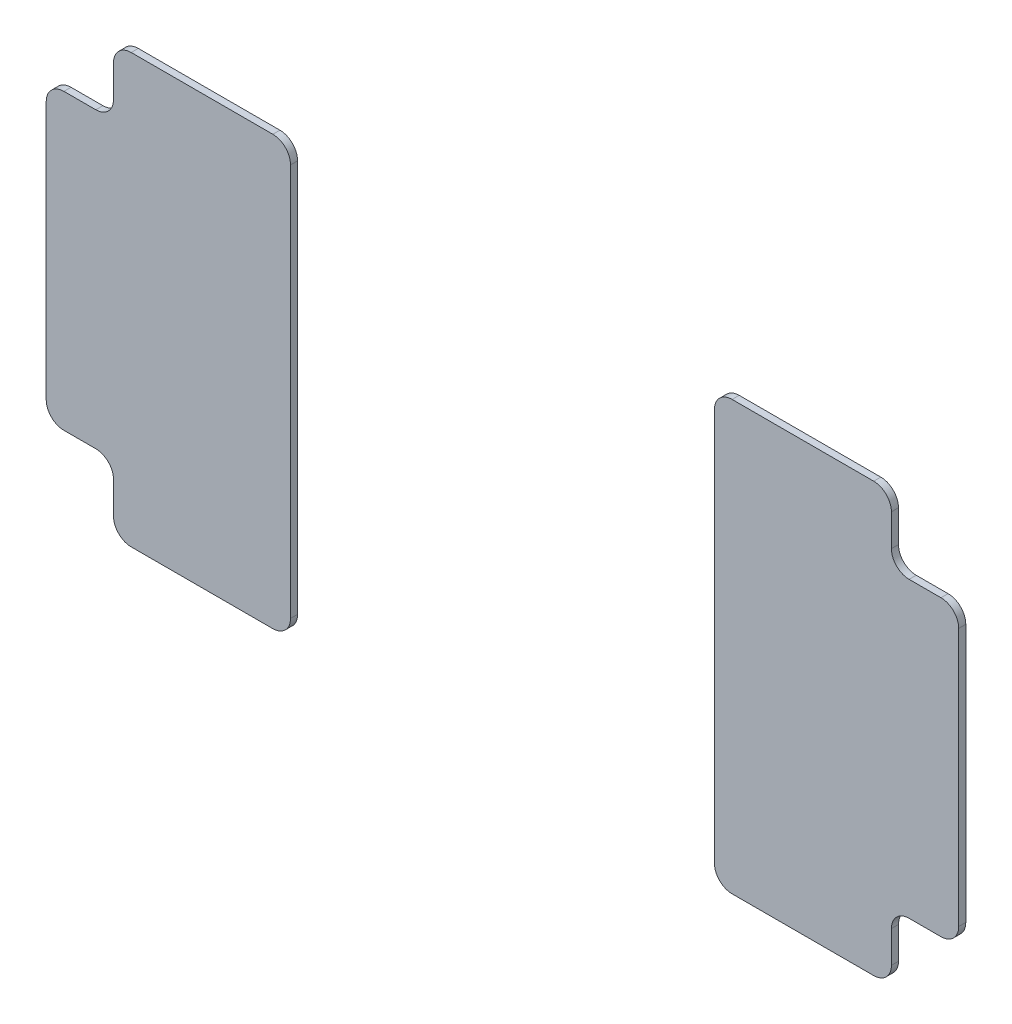
SolidWorks part; units mm, degrees
ref_plane "Front Plane" through (0, 0, 0) normal (0, 0, 1) x (1, 0, 0)
ref_plane "Top Plane" through (0, 0, 0) normal (0, 1, 0) x (1, 0, 0)
ref_plane "Right Plane" through (0, 0, 0) normal (1, 0, 0) x (0, 0, -1)
sketch "Sketch1" plane through (0, 0, 0) normal (0, 0, 1) x (1, 0, 0)
  line L0 (157.8919, 26.2701) -> (191.7747, 29.0915)
  line L1 (157.8919, 26.2701) -> (191.7747, 26.2701)
  line L2 (157.8919, 26.2701) -> (157.8919, 29.0915)
  line L3 (157.8919, 29.0915) -> (191.7747, 29.0915)
  line L4 (191.7747, 26.2701) -> (191.7747, 29.0915)
  line L5 (123.8919, 26.2701) -> (90.0092, 26.2701)
  line L6 (123.8919, 26.2701) -> (123.8919, 29.0915)
  line L7 (123.8919, 29.0915) -> (90.0092, 29.0915)
  line L8 (90.0092, 26.2701) -> (90.0092, 29.0915)
  line L9 (90.0092, 29.0915) -> (123.8919, 26.2701)
  line L10 (168.0919, 58.3601) -> (194.8735, 70.7292)
  line L11 (168.0919, 58.3601) -> (194.8735, 58.3601)
  line L12 (168.0919, 58.3601) -> (168.0919, 70.7292)
  line L13 (168.0919, 70.7292) -> (194.8735, 70.7292)
  line L14 (194.8735, 58.3601) -> (194.8735, 70.7292)
  line L15 (194.8735, 70.7292) -> (224.3587, 70.7292)
  line L16 (194.8735, 70.7292) -> (194.8735, 69.7923)
  line L17 (194.8735, 69.7923) -> (224.3587, 69.7923)
  line L18 (224.3587, 70.7292) -> (224.3587, 69.7923)
  line L19 (224.3587, 69.7923) -> (253.5106, 69.7923)
  line L20 (224.3587, 69.7923) -> (224.3587, 65.2742)
  line L21 (224.3587, 65.2742) -> (253.5106, 65.2742)
  line L22 (253.5106, 69.7923) -> (253.5106, 65.2742)
  line L23 (224.3587, 69.7923) -> (194.8735, 70.7292)
  line L24 (253.5106, 65.2742) -> (224.3587, 69.7923)
  line L25 (170.7502, 87.7401) -> (168.0919, 58.3601)
  line L26 (168.0919, 58.3601) -> (170.7502, 58.3601)
  line L27 (168.0919, 58.3601) -> (168.0919, 87.7401)
  line L28 (168.0919, 87.7401) -> (170.7502, 87.7401)
  line L29 (170.7502, 58.3601) -> (170.7502, 87.7401)
  line L30 (52.9966, 89.4705) -> (24.4119, 82.1791)
  line L31 (24.4119, 82.1791) -> (52.9966, 82.1791)
  line L32 (24.4119, 82.1791) -> (24.4119, 89.4705)
  line L33 (24.4119, 89.4705) -> (52.9966, 89.4705)
  line L34 (52.9966, 82.1791) -> (52.9966, 89.4705)
  line L35 (82.4966, 89.4705) -> (109.0019, 89.4705)
  line L36 (82.4966, 89.4705) -> (82.4966, 76.5201)
  line L37 (82.4966, 76.5201) -> (109.0019, 76.5201)
  line L38 (109.0019, 89.4705) -> (109.0019, 76.5201)
  line L39 (92.4554, 117.2387) -> (82.4966, 117.2387)
  line L40 (92.4554, 117.2387) -> (92.4554, 89.4705)
  line L41 (92.4554, 89.4705) -> (82.4966, 89.4705)
  line L42 (82.4966, 117.2387) -> (82.4966, 89.4705)
  line L43 (92.4554, 117.2387) -> (82.4966, 89.4705)
  line L44 (109.0019, 76.5201) -> (82.4966, 89.4705)
  circle A0 centre (123.8919, 26.2701) radius 14.25
  circle A1 centre (157.8919, 26.2701) radius 14.25
  circle A2 centre (90.0092, 29.0915) radius 14.25
  circle A3 centre (191.7747, 29.0915) radius 14.25
  circle A4 centre (82.4966, 89.4705) radius 11.25
  circle A5 centre (92.4554, 117.2387) radius 11.25
  circle A6 centre (52.9966, 89.4705) radius 11.25
  circle A7 centre (109.0019, 76.5201) radius 11.25
  circle A8 centre (24.4119, 82.1791) radius 11.25
  circle A9 centre (170.7502, 87.7401) radius 11.25
  circle A10 centre (168.0919, 58.3601) radius 11.25
  circle A11 centre (197.5318, 100.1092) radius 11.25
  circle A12 centre (194.8735, 70.7292) radius 11.25
  circle A13 centre (227.0169, 99.1723) radius 11.25
  circle A14 centre (224.3587, 69.7923) radius 11.25
  circle A15 centre (256.1689, 94.6541) radius 11.25
  circle A16 centre (253.5106, 65.2742) radius 11.25
  circle A17 centre (24.4119, 82.1791) radius 12
  circle A18 centre (52.9966, 89.4705) radius 12
  circle A19 centre (92.4554, 117.2387) radius 12
  circle A20 centre (82.4966, 89.4705) radius 12
  circle A21 centre (109.0019, 76.5201) radius 12
  circle A22 centre (168.0919, 58.3601) radius 12
  circle A23 centre (194.8735, 70.7292) radius 12
  circle A24 centre (224.3587, 69.7923) radius 12
  circle A25 centre (253.5106, 65.2742) radius 12
  circle A26 centre (256.1689, 94.6541) radius 12
  circle A27 centre (227.0169, 99.1723) radius 12
  circle A28 centre (197.5318, 100.1092) radius 12
  circle A29 centre (170.7502, 87.7401) radius 12
  circle A30 centre (191.7747, 29.0915) radius 15
  circle A31 centre (157.8919, 26.2701) radius 15
  circle A32 centre (123.8919, 26.2701) radius 15
  circle A33 centre (90.0092, 29.0915) radius 15
  circle A34 centre (173.429, 117.1182) radius 11.25
  circle A35 centre (173.429, 117.1182) radius 12
  dimension "D1" = 28.5
  dimension "D2" = 22.5
  dimension "D3" = 0.75
  dimension "D4" = 0.75
  dimension "D34" = 34
  dimension "D5" = 29.5
  dimension "D6" = 29.5
  dimension "D7" = 29.5
  dimension "D8" = 29.5
  dimension "D9" = 29.5
  dimension "D10" = 29.5
  dimension "D11" = 29.5
  dimension "D12" = 29.5
  dimension "D13" = 29.5
  dimension "D14" = 29.5
  dimension "D15" = 29.5
  dimension "D16" = 29.5
  dimension "D17" = 29.5
  dimension "D18" = 29.5
  dimension "D19" = 34
  dimension "D20" = 34
  dimension "D21" = 32.09
  dimension "D22" = 10.2
  dimension "D23" = 4.76
  dimension "D24" = 4.76
  dimension "D25" = 24.79
  dimension "D26" = 1.82
  dimension "D27" = 8.81
  dimension "D28" = 84.83
  dimension "D29" = 75.69
  dimension "D30" = 70.27
  dimension "D31" = 26.04
  dimension "D32" = 14.89
  dimension "D33" = 50.25
  dimension "D35" = 29.5
  dimension "D36" = 29.5
sketch "Sketch4" plane through (-30.2083, 20.075, 0) normal (0, 0, 1) x (0.9781, -0.2079, 0)
  line L0 (86.1706, 94.1917) -> (105.2206, 75.1417)
  line L1 (67.1206, 94.1917) -> (86.1706, 94.1917)
  line L2 (67.1206, 94.1917) -> (67.1206, 75.1417)
  line L3 (67.1206, 75.1417) -> (86.1706, 75.1417)
  line L4 (86.1706, 94.1917) -> (86.1706, 75.1417)
  line L5 (86.1706, 94.1917) -> (105.2206, 94.1917)
  line L6 (86.1706, 94.1917) -> (86.1706, 75.1417)
  line L7 (86.1706, 75.1417) -> (105.2206, 75.1417)
  line L8 (105.2206, 94.1917) -> (105.2206, 75.1417)
  line L9 (105.2206, 94.1917) -> (124.2706, 94.1917)
  line L10 (105.2206, 94.1917) -> (105.2206, 75.1417)
  line L11 (105.2206, 75.1417) -> (124.2706, 75.1417)
  line L12 (124.2706, 94.1917) -> (124.2706, 75.1417)
  line L13 (86.1706, 94.1917) -> (105.2206, 94.1917)
  line L14 (86.1706, 94.1917) -> (86.1706, 113.2417)
  line L15 (86.1706, 113.2417) -> (105.2206, 113.2417)
  line L16 (105.2206, 94.1917) -> (105.2206, 113.2417)
  line L17 (66.9585, 85.1784) -> (124.4326, 84.1551)
  point P14 (95.6956, 84.6667)
  point P15 (95.6956, 84.6667)
  dimension "D1" = 19.05
sketch "Sketch9" plane through (0, 0, 0) normal (0, 0, 1) x (1, 0, 0)
  line L1 (17.3619, 89.2291) -> (31.4619, 89.2291)
  line L2 (17.3619, 89.2291) -> (17.3619, 75.1291)
  line L3 (17.3619, 75.1291) -> (31.4619, 75.1291)
  line L4 (31.4619, 89.2291) -> (31.4619, 75.1291)
  line L5 (45.9466, 96.5205) -> (60.0466, 96.5205)
  line L6 (45.9466, 96.5205) -> (45.9466, 82.4205)
  line L7 (45.9466, 82.4205) -> (60.0466, 82.4205)
  line L8 (60.0466, 96.5205) -> (60.0466, 82.4205)
  line L9 (75.4466, 96.5205) -> (89.5466, 96.5205)
  line L10 (75.4466, 96.5205) -> (75.4466, 82.4205)
  line L11 (75.4466, 82.4205) -> (89.5466, 82.4205)
  line L12 (89.5466, 96.5205) -> (89.5466, 82.4205)
  line L13 (101.9519, 83.5701) -> (116.0519, 83.5701)
  line L14 (101.9519, 83.5701) -> (101.9519, 69.4701)
  line L15 (101.9519, 69.4701) -> (116.0519, 69.4701)
  line L16 (116.0519, 83.5701) -> (116.0519, 69.4701)
  line L17 (85.4054, 124.2887) -> (99.5054, 124.2887)
  line L18 (85.4054, 124.2887) -> (85.4054, 110.1887)
  line L19 (85.4054, 110.1887) -> (99.5054, 110.1887)
  line L20 (99.5054, 124.2887) -> (99.5054, 110.1887)
  line L21 (82.9592, 36.1415) -> (97.0592, 36.1415)
  line L22 (82.9592, 36.1415) -> (82.9592, 22.0415)
  line L23 (82.9592, 22.0415) -> (97.0592, 22.0415)
  line L24 (97.0592, 36.1415) -> (97.0592, 22.0415)
  line L25 (116.8419, 33.3201) -> (130.9419, 33.3201)
  line L26 (116.8419, 33.3201) -> (116.8419, 19.2201)
  line L27 (116.8419, 19.2201) -> (130.9419, 19.2201)
  line L28 (130.9419, 33.3201) -> (130.9419, 19.2201)
  line L29 (150.8419, 33.3201) -> (164.9419, 33.3201)
  line L30 (150.8419, 33.3201) -> (150.8419, 19.2201)
  line L31 (150.8419, 19.2201) -> (164.9419, 19.2201)
  line L32 (164.9419, 33.3201) -> (164.9419, 19.2201)
  line L33 (184.7247, 36.1415) -> (198.8247, 36.1415)
  line L34 (184.7247, 36.1415) -> (184.7247, 22.0415)
  line L35 (184.7247, 22.0415) -> (198.8247, 22.0415)
  line L36 (198.8247, 36.1415) -> (198.8247, 22.0415)
  line L37 (260.5606, 58.2242) -> (246.4606, 58.2242)
  line L38 (260.5606, 58.2242) -> (260.5606, 72.3242)
  line L39 (260.5606, 72.3242) -> (246.4606, 72.3242)
  line L40 (246.4606, 58.2242) -> (246.4606, 72.3242)
  line L41 (217.3087, 76.8423) -> (231.4087, 76.8423)
  line L42 (217.3087, 76.8423) -> (217.3087, 62.7423)
  line L43 (217.3087, 62.7423) -> (231.4087, 62.7423)
  line L44 (231.4087, 76.8423) -> (231.4087, 62.7423)
  line L45 (187.8235, 77.7792) -> (201.9235, 77.7792)
  line L46 (187.8235, 77.7792) -> (187.8235, 63.6792)
  line L47 (187.8235, 63.6792) -> (201.9235, 63.6792)
  line L48 (201.9235, 77.7792) -> (201.9235, 63.6792)
  line L49 (161.0419, 65.4101) -> (175.1419, 65.4101)
  line L50 (161.0419, 65.4101) -> (161.0419, 51.3101)
  line L51 (161.0419, 51.3101) -> (175.1419, 51.3101)
  line L52 (175.1419, 65.4101) -> (175.1419, 51.3101)
  line L53 (163.7002, 94.7901) -> (177.8002, 94.7901)
  line L54 (163.7002, 94.7901) -> (163.7002, 80.6901)
  line L55 (163.7002, 80.6901) -> (177.8002, 80.6901)
  line L56 (177.8002, 94.7901) -> (177.8002, 80.6901)
  line L57 (190.4818, 107.1592) -> (204.5818, 107.1592)
  line L58 (190.4818, 107.1592) -> (190.4818, 93.0592)
  line L59 (190.4818, 93.0592) -> (204.5818, 93.0592)
  line L60 (204.5818, 107.1592) -> (204.5818, 93.0592)
  line L61 (219.9669, 106.2223) -> (234.0669, 106.2223)
  line L62 (219.9669, 106.2223) -> (219.9669, 92.1223)
  line L63 (219.9669, 92.1223) -> (234.0669, 92.1223)
  line L64 (234.0669, 106.2223) -> (234.0669, 92.1223)
  line L65 (249.1189, 101.7041) -> (263.2189, 101.7041)
  line L66 (249.1189, 101.7041) -> (249.1189, 87.6041)
  line L67 (249.1189, 87.6041) -> (263.2189, 87.6041)
  line L68 (263.2189, 101.7041) -> (263.2189, 87.6041)
  line L69 (166.379, 124.1682) -> (180.479, 124.1682)
  line L70 (166.379, 124.1682) -> (166.379, 110.0682)
  line L71 (166.379, 110.0682) -> (180.479, 110.0682)
  line L72 (180.479, 124.1682) -> (180.479, 110.0682)
  point P72 (24.4119, 89.2291)
  point P74 (52.9966, 96.5205)
  point P76 (82.4966, 96.5205)
  point P78 (92.4554, 124.2887)
  point P80 (109.0019, 83.5701)
  point P82 (90.0092, 36.1415)
  point P84 (123.8919, 33.3201)
  point P86 (157.8919, 33.3201)
  point P88 (191.7747, 36.1415)
  point P90 (168.0919, 65.4101)
  point P92 (170.7502, 94.7901)
  point P94 (173.429, 124.1682)
  point P96 (197.5318, 107.1592)
  point P98 (227.0169, 106.2223)
  point P100 (256.1689, 101.7041)
  point P102 (194.8735, 77.7792)
  point P104 (224.3587, 76.8423)
  point P106 (253.5106, 72.3242)
  point P108 (17.3619, 82.1791)
  point P109 (45.9466, 89.4705)
  point P110 (75.4466, 89.4705)
  point P111 (101.9519, 76.5201)
  point P112 (85.4054, 117.2387)
  point P113 (82.9592, 29.0915)
  point P114 (116.8419, 26.2701)
  point P115 (150.8419, 26.2701)
  point P116 (184.7247, 29.0915)
  point P118 (161.0419, 58.3601)
  point P119 (187.8235, 70.7292)
  point P120 (217.3087, 69.7923)
  point P121 (246.4606, 65.2742)
  point P122 (163.7002, 87.7401)
  point P123 (190.4818, 100.1092)
  point P124 (219.9669, 99.1723)
  point P125 (249.1189, 94.6541)
  point P126 (166.379, 117.1182)
  dimension "D1" = 14.1
sketch "Sketch10" plane through (-22.0981, 19.3454, 0) normal (0, 0, 1) x (0.9781, -0.2079, 0)
  line L1 (61.5108, 90.7441) -> (75.6108, 90.7441)
  line L2 (61.5108, 90.7441) -> (61.5108, 76.6441)
  line L3 (61.5108, 76.6441) -> (75.6108, 76.6441)
  line L4 (75.6108, 90.7441) -> (75.6108, 76.6441)
  line L5 (80.5608, 90.7441) -> (94.6608, 90.7441)
  line L6 (80.5608, 90.7441) -> (80.5608, 76.6441)
  line L7 (80.5608, 76.6441) -> (94.6608, 76.6441)
  line L8 (94.6608, 90.7441) -> (94.6608, 76.6441)
  line L9 (99.6108, 90.7441) -> (113.7108, 90.7441)
  line L10 (99.6108, 90.7441) -> (99.6108, 76.6441)
  line L11 (99.6108, 76.6441) -> (113.7108, 76.6441)
  line L12 (113.7108, 90.7441) -> (113.7108, 76.6441)
  line L13 (80.5608, 109.7941) -> (94.6608, 109.7941)
  line L14 (80.5608, 109.7941) -> (80.5608, 95.6941)
  line L15 (80.5608, 95.6941) -> (94.6608, 95.6941)
  line L16 (94.6608, 109.7941) -> (94.6608, 95.6941)
  line L17 (50.5121, 89.6359) -> (53.4436, 75.8441) construction
  line L18 (59.0358, 93.2191) -> (78.0858, 93.2191) construction
  line L19 (78.0858, 112.2691) -> (97.1358, 112.2691) construction
  line L20 (97.1358, 93.2191) -> (116.1858, 93.2191) construction
  line L21 (78.0858, 93.2191) -> (78.0858, 112.2691) construction
  line L23 (59.0358, 93.2191) -> (59.0358, 74.1691) construction
  point P16 (75.6108, 83.6941)
  point P17 (94.6608, 83.6941)
  point P18 (113.7108, 83.6941)
  point P19 (87.6108, 90.7441)
  point P20 (87.6108, 109.7941)
  point P23 (68.5608, 90.7441)
  point P26 (68.5608, 93.2191)
  point P29 (87.6108, 112.2691)
  point P30 (106.6608, 90.7441)
  point P33 (106.6608, 93.2191)
  point P34 (80.5608, 102.7441)
  point P37 (78.0858, 102.7441)
  point P42 (59.0358, 83.6941)
  point P43 (61.5108, 83.6941)
sketch "Sketch14" plane through (0, 0, 0) normal (0, 0, 1) x (1, 0, 0)
  line L0 (165.1144, 80.6901) -> (163.7002, 82.1043)
  line L1 (163.7002, 93.3758) -> (165.1144, 94.7901)
  line L2 (177.8002, 93.3758) -> (176.386, 94.7901)
  line L3 (179.0648, 110.0682) -> (180.479, 111.4824)
  line L4 (166.379, 111.4824) -> (167.7932, 110.0682)
  line L5 (166.379, 122.754) -> (167.7932, 124.1682)
  line L6 (179.0648, 124.1682) -> (180.479, 122.754)
  line L7 (203.1676, 93.0592) -> (204.5818, 94.4734)
  line L8 (17.3619, 89.2291) -> (17.3619, 75.1291) construction
  line L9 (17.3619, 89.2291) -> (31.4619, 89.2291) construction
  line L10 (17.3619, 87.8149) -> (18.7761, 89.2291)
  line L11 (17.3619, 75.1291) -> (31.4619, 75.1291) construction
  line L12 (31.4619, 89.2291) -> (31.4619, 75.1291) construction
  line L13 (45.9466, 96.5205) -> (60.0466, 96.5205) construction
  line L14 (60.0466, 96.5205) -> (60.0466, 82.4205) construction
  line L15 (45.9466, 96.5205) -> (45.9466, 82.4205) construction
  line L16 (45.9466, 82.4205) -> (60.0466, 82.4205) construction
  line L17 (85.4054, 124.2887) -> (85.4054, 110.1887) construction
  line L18 (85.4054, 124.2887) -> (99.5054, 124.2887) construction
  line L19 (99.5054, 124.2887) -> (99.5054, 110.1887) construction
  line L20 (85.4054, 110.1887) -> (99.5054, 110.1887) construction
  line L21 (101.9519, 83.5701) -> (101.9519, 69.4701) construction
  line L22 (101.9519, 83.5701) -> (116.0519, 83.5701) construction
  line L23 (116.0519, 83.5701) -> (116.0519, 69.4701) construction
  line L24 (101.9519, 69.4701) -> (116.0519, 69.4701) construction
  line L25 (91.2712, 73.6044) -> (105.0631, 70.6729) construction
  line L26 (107.9947, 84.4647) -> (105.0631, 70.6729) construction
  line L27 (94.2028, 87.3963) -> (107.9947, 84.4647) construction
  line L28 (94.2028, 87.3963) -> (91.2712, 73.6044) construction
  line L29 (72.6375, 77.5651) -> (86.4294, 74.6336) construction
  line L30 (89.361, 88.4255) -> (86.4294, 74.6336) construction
  line L31 (75.5691, 91.357) -> (89.361, 88.4255) construction
  line L32 (75.5691, 91.357) -> (72.6375, 77.5651) construction
  line L33 (56.9354, 95.3177) -> (54.0038, 81.5259) construction
  line L34 (56.9354, 95.3177) -> (70.7273, 92.3862) construction
  line L35 (70.7273, 92.3862) -> (67.7957, 78.5943) construction
  line L36 (54.0038, 81.5259) -> (67.7957, 78.5943) construction
  line L37 (76.5983, 96.1988) -> (90.3901, 93.2673) construction
  line L38 (93.3217, 107.0592) -> (90.3901, 93.2673) construction
  line L39 (79.5298, 109.9907) -> (76.5983, 96.1988) construction
  line L40 (79.5298, 109.9907) -> (93.3217, 107.0592) construction
  line L41 (82.9592, 36.1415) -> (82.9592, 22.0415) construction
  line L42 (82.9592, 36.1415) -> (97.0592, 36.1415) construction
  line L43 (82.9592, 22.0415) -> (97.0592, 22.0415) construction
  line L44 (97.0592, 36.1415) -> (97.0592, 22.0415) construction
  line L45 (116.8419, 33.3201) -> (116.8419, 19.2201) construction
  line L46 (116.8419, 33.3201) -> (130.9419, 33.3201) construction
  line L47 (116.8419, 19.2201) -> (130.9419, 19.2201) construction
  line L48 (130.9419, 33.3201) -> (130.9419, 19.2201) construction
  line L49 (150.8419, 33.3201) -> (150.8419, 19.2201) construction
  line L50 (150.8419, 33.3201) -> (164.9419, 33.3201) construction
  line L51 (164.9419, 33.3201) -> (164.9419, 19.2201) construction
  line L52 (150.8419, 19.2201) -> (164.9419, 19.2201) construction
  line L53 (184.7247, 36.1415) -> (184.7247, 22.0415) construction
  line L54 (184.7247, 22.0415) -> (198.8247, 22.0415) construction
  line L55 (198.8247, 36.1415) -> (198.8247, 22.0415) construction
  line L56 (184.7247, 36.1415) -> (198.8247, 36.1415) construction
  line L57 (161.0419, 65.4101) -> (175.1419, 65.4101) construction
  line L58 (175.1419, 65.4101) -> (175.1419, 51.3101) construction
  line L59 (161.0419, 51.3101) -> (175.1419, 51.3101) construction
  line L60 (161.0419, 65.4101) -> (161.0419, 51.3101) construction
  line L61 (187.8235, 77.7792) -> (187.8235, 63.6792) construction
  line L62 (187.8235, 77.7792) -> (201.9235, 77.7792) construction
  line L63 (187.8235, 63.6792) -> (201.9235, 63.6792) construction
  line L64 (201.9235, 77.7792) -> (201.9235, 63.6792) construction
  line L65 (217.3087, 76.8423) -> (217.3087, 62.7423) construction
  line L66 (217.3087, 76.8423) -> (231.4087, 76.8423) construction
  line L67 (231.4087, 76.8423) -> (231.4087, 62.7423) construction
  line L68 (217.3087, 62.7423) -> (231.4087, 62.7423) construction
  line L69 (260.5606, 58.2242) -> (246.4606, 58.2242) construction
  line L70 (260.5606, 58.2242) -> (260.5606, 72.3242) construction
  line L71 (246.4606, 58.2242) -> (246.4606, 72.3242) construction
  line L72 (260.5606, 72.3242) -> (246.4606, 72.3242) construction
  line L73 (249.1189, 101.7041) -> (263.2189, 101.7041) construction
  line L74 (263.2189, 101.7041) -> (263.2189, 87.6041) construction
  line L75 (249.1189, 87.6041) -> (263.2189, 87.6041) construction
  line L76 (249.1189, 101.7041) -> (249.1189, 87.6041) construction
  line L77 (219.9669, 106.2223) -> (219.9669, 92.1223) construction
  line L78 (219.9669, 106.2223) -> (234.0669, 106.2223) construction
  line L79 (234.0669, 106.2223) -> (234.0669, 92.1223) construction
  line L80 (219.9669, 92.1223) -> (234.0669, 92.1223) construction
  line L81 (190.4818, 107.1592) -> (204.5818, 107.1592) construction
  line L82 (204.5818, 107.1592) -> (204.5818, 93.0592) construction
  line L83 (190.4818, 93.0592) -> (204.5818, 93.0592) construction
  line L84 (190.4818, 107.1592) -> (190.4818, 93.0592) construction
  line L85 (163.7002, 94.7901) -> (177.8002, 94.7901) construction
  line L86 (177.8002, 94.7901) -> (177.8002, 80.6901) construction
  line L87 (163.7002, 80.6901) -> (177.8002, 80.6901) construction
  line L88 (163.7002, 94.7901) -> (163.7002, 80.6901) construction
  line L89 (180.479, 124.1682) -> (180.479, 110.0682) construction
  line L90 (166.379, 110.0682) -> (180.479, 110.0682) construction
  line L91 (166.379, 124.1682) -> (166.379, 110.0682) construction
  line L92 (166.379, 124.1682) -> (180.479, 124.1682) construction
  line L93 (17.3619, 76.5433) -> (18.7761, 75.1291)
  line L94 (30.0477, 75.1291) -> (31.4619, 76.5433)
  line L95 (31.4619, 87.8149) -> (30.0477, 89.2291)
  line L96 (45.9466, 95.1063) -> (47.3608, 96.5205)
  line L97 (45.9466, 83.8347) -> (47.3608, 82.4205)
  line L98 (54.2979, 82.9092) -> (55.3871, 81.2318)
  line L99 (58.6323, 82.4205) -> (60.0466, 83.8347)
  line L100 (56.6413, 93.9344) -> (58.3187, 95.0237)
  line L101 (58.6323, 96.5205) -> (60.0466, 95.1063)
  line L102 (69.3439, 92.6802) -> (70.4332, 91.0029)
  line L103 (68.0897, 79.9776) -> (66.4124, 78.8883)
  line L104 (75.2751, 89.9737) -> (76.9524, 91.063)
  line L105 (72.9316, 78.9484) -> (74.0208, 77.2711)
  line L106 (85.0461, 74.9276) -> (86.7234, 76.0169)
  line L107 (89.0669, 87.0421) -> (87.9777, 88.7195)
  line L108 (89.0068, 93.5613) -> (90.6842, 94.6506)
  line L109 (76.8923, 97.5822) -> (77.9816, 95.9048)
  line L110 (91.9384, 107.3532) -> (93.0277, 105.6759)
  line L111 (79.2358, 108.6074) -> (80.9131, 109.6967)
  line L112 (85.4054, 111.6029) -> (86.8196, 110.1887)
  line L113 (98.0912, 110.1887) -> (99.5054, 111.6029)
  line L114 (98.0912, 124.2887) -> (99.5054, 122.8745)
  line L115 (85.4054, 122.8745) -> (86.8196, 124.2887)
  line L116 (93.9088, 86.013) -> (95.5861, 87.1023)
  line L117 (91.5653, 74.9877) -> (92.6546, 73.3104)
  line L118 (103.6798, 70.9669) -> (105.3572, 72.0562)
  line L119 (106.6114, 84.7588) -> (107.7006, 83.0814)
  line L120 (101.9519, 82.1559) -> (103.3662, 83.5701)
  line L121 (101.9519, 70.8843) -> (103.3662, 69.4701)
  line L122 (114.6377, 69.4701) -> (116.0519, 70.8843)
  line L123 (116.0519, 82.1559) -> (114.6377, 83.5701)
  line L124 (82.9592, 34.7272) -> (84.3734, 36.1415)
  line L125 (82.9592, 23.4557) -> (84.3734, 22.0415)
  line L126 (95.645, 22.0415) -> (97.0592, 23.4557)
  line L127 (97.0592, 34.7272) -> (95.645, 36.1415)
  line L128 (116.8419, 31.9059) -> (118.2562, 33.3201)
  line L129 (116.8419, 20.6343) -> (118.2562, 19.2201)
  line L130 (129.5277, 19.2201) -> (130.9419, 20.6343)
  line L131 (130.9419, 31.9059) -> (129.5277, 33.3201)
  line L132 (150.8419, 31.9059) -> (152.2562, 33.3201)
  line L133 (150.8419, 20.6343) -> (152.2562, 19.2201)
  line L134 (163.5277, 19.2201) -> (164.9419, 20.6343)
  line L135 (164.9419, 31.9059) -> (163.5277, 33.3201)
  line L136 (184.7247, 34.7272) -> (186.1389, 36.1415)
  line L137 (184.7247, 23.4557) -> (186.1389, 22.0415)
  line L138 (197.4105, 22.0415) -> (198.8247, 23.4557)
  line L139 (198.8247, 34.7272) -> (197.4105, 36.1415)
  line L140 (173.7277, 51.3101) -> (175.1419, 52.7243)
  line L141 (161.0419, 52.7243) -> (162.4562, 51.3101)
  line L142 (161.0419, 63.9959) -> (162.4562, 65.4101)
  line L143 (173.7277, 65.4101) -> (175.1419, 63.9959)
  line L144 (187.8235, 65.0934) -> (189.2378, 63.6792)
  line L145 (200.5093, 63.6792) -> (201.9235, 65.0934)
  line L146 (200.5093, 77.7792) -> (201.9235, 76.365)
  line L147 (187.8235, 76.365) -> (189.2378, 77.7792)
  line L148 (176.386, 80.6901) -> (177.8002, 82.1043)
  line L149 (204.5818, 105.745) -> (203.1676, 107.1592)
  line L150 (191.896, 107.1592) -> (190.4818, 105.745)
  line L151 (190.4818, 94.4734) -> (191.896, 93.0592)
  line L152 (219.9669, 104.8081) -> (221.3812, 106.2223)
  line L153 (232.6527, 106.2223) -> (234.0669, 104.8081)
  line L154 (234.0669, 93.5365) -> (232.6527, 92.1223)
  line L155 (219.9669, 93.5365) -> (221.3812, 92.1223)
  line L156 (229.9944, 76.8423) -> (231.4087, 75.4281)
  line L157 (217.3087, 75.4281) -> (218.7229, 76.8423)
  line L158 (217.3087, 64.1565) -> (218.7229, 62.7423)
  line L159 (229.9944, 62.7423) -> (231.4087, 64.1565)
  line L160 (259.1464, 72.3242) -> (260.5606, 70.9099)
  line L161 (246.4606, 70.9099) -> (247.8748, 72.3242)
  line L162 (259.1464, 58.2242) -> (260.5606, 59.6384)
  line L163 (247.8748, 58.2242) -> (246.4606, 59.6384)
  line L164 (261.8047, 87.6041) -> (263.2189, 89.0183)
  line L165 (249.1189, 89.0183) -> (250.5331, 87.6041)
  line L166 (249.1189, 100.2899) -> (250.5331, 101.7041)
  line L167 (261.8047, 101.7041) -> (263.2189, 100.2899)
  line L168 (75.4466, 96.5205) -> (75.4466, 82.4205) construction
  line L169 (75.4466, 96.5205) -> (89.5466, 96.5205) construction
  line L170 (89.5466, 96.5205) -> (89.5466, 82.4205) construction
  line L171 (75.4466, 82.4205) -> (89.5466, 82.4205) construction
  line L172 (76.8608, 96.5205) -> (75.4466, 95.1063)
  line L173 (88.1323, 96.5205) -> (89.5466, 95.1063)
  line L174 (89.5466, 83.8347) -> (88.1323, 82.4205)
  line L175 (75.4466, 83.8347) -> (76.8608, 82.4205)
  arc A0 (17.3619, 87.8149) -> (18.7761, 89.2291) centre (18.069, 88.522) cw
  arc A1 (18.7761, 75.1291) -> (17.3619, 76.5433) centre (18.069, 75.8362) cw
  arc A2 (31.4619, 76.5433) -> (30.0477, 75.1291) centre (30.7548, 75.8362) cw
  arc A3 (30.0477, 89.2291) -> (31.4619, 87.8149) centre (30.7548, 88.522) cw
  arc A4 (58.6323, 96.5205) -> (60.0466, 95.1063) centre (59.3394, 95.8134) cw
  arc A5 (45.9466, 95.1063) -> (47.3608, 96.5205) centre (46.6537, 95.8134) cw
  arc A6 (47.3608, 82.4205) -> (45.9466, 83.8347) centre (46.6537, 83.1276) cw
  arc A7 (60.0466, 83.8347) -> (58.6323, 82.4205) centre (59.3394, 83.1276) cw
  arc A8 (85.4054, 122.8745) -> (86.8196, 124.2887) centre (86.1125, 123.5816) cw
  arc A9 (98.0912, 124.2887) -> (99.5054, 122.8745) centre (98.7983, 123.5816) cw
  arc A10 (99.5054, 111.6029) -> (98.0912, 110.1887) centre (98.7983, 110.8958) cw
  arc A11 (85.4054, 111.6029) -> (86.8196, 110.1887) centre (86.1125, 110.8958) ccw
  arc A12 (101.9519, 82.1559) -> (103.3662, 83.5701) centre (102.6591, 82.863) cw
  arc A13 (114.6377, 83.5701) -> (116.0519, 82.1559) centre (115.3448, 82.863) cw
  arc A14 (116.0519, 70.8843) -> (114.6377, 69.4701) centre (115.3448, 70.1772) cw
  arc A15 (101.9519, 70.8843) -> (103.3662, 69.4701) centre (102.6591, 70.1772) ccw
  arc A16 (103.6798, 70.9669) -> (105.3572, 72.0562) centre (104.5185, 71.5115) ccw
  arc A17 (106.6114, 84.7588) -> (107.7006, 83.0814) centre (107.156, 83.9201) cw
  arc A18 (93.9088, 86.013) -> (95.5861, 87.1023) centre (94.7474, 86.5576) cw
  arc A19 (91.5653, 74.9877) -> (92.6546, 73.3104) centre (92.1099, 74.1491) ccw
  arc A20 (85.0461, 74.9276) -> (86.7234, 76.0169) centre (85.8848, 75.4722) ccw
  arc A21 (87.9777, 88.7195) -> (89.0669, 87.0421) centre (88.5223, 87.8808) cw
  arc A22 (75.2751, 89.9737) -> (76.9524, 91.063) centre (76.1137, 90.5183) cw
  arc A23 (72.9316, 78.9484) -> (74.0208, 77.2711) centre (73.4762, 78.1098) ccw
  arc A24 (56.6413, 93.9344) -> (58.3187, 95.0237) centre (57.48, 94.4791) cw
  arc A25 (69.3439, 92.6802) -> (70.4332, 91.0029) centre (69.8886, 91.8415) cw
  arc A26 (68.0897, 79.9776) -> (66.4124, 78.8883) centre (67.2511, 79.433) cw
  arc A27 (54.2979, 82.9092) -> (55.3871, 81.2318) centre (54.8425, 82.0705) ccw
  arc A28 (89.0068, 93.5613) -> (90.6842, 94.6506) centre (89.8455, 94.106) ccw
  arc A29 (76.8923, 97.5822) -> (77.9816, 95.9048) centre (77.4369, 96.7435) ccw
  arc A30 (79.2358, 108.6074) -> (80.9131, 109.6967) centre (80.0744, 109.1521) cw
  arc A31 (91.9384, 107.3532) -> (93.0277, 105.6759) centre (92.483, 106.5145) cw
  arc A32 (82.9592, 34.7272) -> (84.3734, 36.1415) centre (83.6663, 35.4344) cw
  arc A33 (82.9592, 23.4557) -> (84.3734, 22.0415) centre (83.6663, 22.7486) ccw
  arc A34 (95.645, 22.0415) -> (97.0592, 23.4557) centre (96.3521, 22.7486) ccw
  arc A35 (95.645, 36.1415) -> (97.0592, 34.7272) centre (96.3521, 35.4344) cw
  arc A36 (116.8419, 31.9059) -> (118.2562, 33.3201) centre (117.5491, 32.613) cw
  arc A37 (116.8419, 20.6343) -> (118.2562, 19.2201) centre (117.5491, 19.9272) ccw
  arc A38 (129.5277, 19.2201) -> (130.9419, 20.6343) centre (130.2348, 19.9272) ccw
  arc A39 (129.5277, 33.3201) -> (130.9419, 31.9059) centre (130.2348, 32.613) cw
  arc A40 (150.8419, 31.9059) -> (152.2562, 33.3201) centre (151.5491, 32.613) cw
  arc A41 (163.5277, 33.3201) -> (164.9419, 31.9059) centre (164.2348, 32.613) cw
  arc A42 (164.9419, 20.6343) -> (163.5277, 19.2201) centre (164.2348, 19.9272) cw
  arc A43 (150.8419, 20.6343) -> (152.2562, 19.2201) centre (151.5491, 19.9272) ccw
  arc A44 (184.7247, 23.4557) -> (186.1389, 22.0415) centre (185.4318, 22.7486) ccw
  arc A45 (197.4105, 22.0415) -> (198.8247, 23.4557) centre (198.1176, 22.7486) ccw
  arc A46 (197.4105, 36.1415) -> (198.8247, 34.7272) centre (198.1176, 35.4344) cw
  arc A47 (184.7247, 34.7272) -> (186.1389, 36.1415) centre (185.4318, 35.4344) cw
  arc A48 (173.7277, 65.4101) -> (175.1419, 63.9959) centre (174.4348, 64.703) cw
  arc A49 (175.1419, 52.7243) -> (173.7277, 51.3101) centre (174.4348, 52.0172) cw
  arc A50 (161.0419, 52.7243) -> (162.4562, 51.3101) centre (161.7491, 52.0172) ccw
  arc A51 (161.0419, 63.9959) -> (162.4562, 65.4101) centre (161.7491, 64.703) cw
  arc A52 (187.8235, 76.365) -> (189.2378, 77.7792) centre (188.5306, 77.0721) cw
  arc A53 (187.8235, 65.0934) -> (189.2378, 63.6792) centre (188.5306, 64.3863) ccw
  arc A54 (200.5093, 63.6792) -> (201.9235, 65.0934) centre (201.2164, 64.3863) ccw
  arc A55 (200.5093, 77.7792) -> (201.9235, 76.365) centre (201.2164, 77.0721) cw
  arc A56 (217.3087, 75.4281) -> (218.7229, 76.8423) centre (218.0158, 76.1352) cw
  arc A57 (229.9944, 76.8423) -> (231.4087, 75.4281) centre (230.7016, 76.1352) cw
  arc A58 (231.4087, 64.1565) -> (229.9944, 62.7423) centre (230.7016, 63.4494) cw
  arc A59 (217.3087, 64.1565) -> (218.7229, 62.7423) centre (218.0158, 63.4494) ccw
  arc A60 (259.1464, 58.2242) -> (260.5606, 59.6384) centre (259.8535, 58.9313) ccw
  arc A61 (246.4606, 59.6384) -> (247.8748, 58.2242) centre (247.1677, 58.9313) ccw
  arc A62 (246.4606, 70.9099) -> (247.8748, 72.3242) centre (247.1677, 71.617) cw
  arc A63 (259.1464, 72.3242) -> (260.5606, 70.9099) centre (259.8535, 71.617) cw
  arc A64 (261.8047, 101.7041) -> (263.2189, 100.2899) centre (262.5118, 100.997) cw
  arc A65 (263.2189, 89.0183) -> (261.8047, 87.6041) centre (262.5118, 88.3112) cw
  arc A66 (250.5331, 87.6041) -> (249.1189, 89.0183) centre (249.826, 88.3112) cw
  arc A67 (249.1189, 100.2899) -> (250.5331, 101.7041) centre (249.826, 100.997) cw
  arc A68 (219.9669, 104.8081) -> (221.3812, 106.2223) centre (220.674, 105.5152) cw
  arc A69 (232.6527, 106.2223) -> (234.0669, 104.8081) centre (233.3598, 105.5152) cw
  arc A70 (234.0669, 93.5365) -> (232.6527, 92.1223) centre (233.3598, 92.8294) cw
  arc A71 (221.3812, 92.1223) -> (219.9669, 93.5365) centre (220.674, 92.8294) cw
  arc A72 (203.1676, 107.1592) -> (204.5818, 105.745) centre (203.8747, 106.4521) cw
  arc A73 (204.5818, 94.4734) -> (203.1676, 93.0592) centre (203.8747, 93.7663) cw
  arc A74 (191.896, 93.0592) -> (190.4818, 94.4734) centre (191.1889, 93.7663) cw
  arc A75 (190.4818, 105.745) -> (191.896, 107.1592) centre (191.1889, 106.4521) cw
  arc A76 (176.386, 94.7901) -> (177.8002, 93.3758) centre (177.0931, 94.0829) cw
  arc A77 (177.8002, 82.1043) -> (176.386, 80.6901) centre (177.0931, 81.3972) cw
  arc A78 (165.1144, 80.6901) -> (163.7002, 82.1043) centre (164.4073, 81.3972) cw
  arc A79 (163.7002, 93.3758) -> (165.1144, 94.7901) centre (164.4073, 94.0829) cw
  arc A80 (180.479, 111.4824) -> (179.0648, 110.0682) centre (179.7719, 110.7753) cw
  arc A81 (167.7932, 110.0682) -> (166.379, 111.4824) centre (167.0861, 110.7753) cw
  arc A82 (179.0648, 124.1682) -> (180.479, 122.754) centre (179.7719, 123.4611) cw
  arc A83 (166.379, 122.754) -> (167.7932, 124.1682) centre (167.0861, 123.4611) cw
  arc A84 (75.4466, 95.1063) -> (76.8608, 96.5205) centre (76.1537, 95.8134) cw
  arc A85 (88.1323, 96.5205) -> (89.5466, 95.1063) centre (88.8394, 95.8134) cw
  arc A86 (89.5466, 83.8347) -> (88.1323, 82.4205) centre (88.8394, 83.1276) cw
  arc A87 (76.8608, 82.4205) -> (75.4466, 83.8347) centre (76.1537, 83.1276) cw
  dimension "D1" = 45
  dimension "D2" = 1
  dimension "D71" = 45
  dimension "D3" = 45
  dimension "D4" = 45
  dimension "D5" = 45
  dimension "D6" = 45
  dimension "D7" = 45
  dimension "D8" = 45
  dimension "D9" = 45
  dimension "D10" = 45
  dimension "D11" = 45
  dimension "D12" = 45
  dimension "D13" = 45
  dimension "D14" = 45
  dimension "D15" = 45
  dimension "D16" = 45
  dimension "D17" = 45
  dimension "D18" = 45
  dimension "D19" = 45
  dimension "D20" = 45
  dimension "D21" = 45
  dimension "D22" = 45
  dimension "D23" = 45
  dimension "D24" = 45
  dimension "D25" = 45
  dimension "D26" = 45
  dimension "D27" = 45
  dimension "D28" = 45
  dimension "D29" = 45
  dimension "D30" = 45
  dimension "D31" = 45
  dimension "D32" = 45
  dimension "D33" = 45
  dimension "D34" = 45
  dimension "D35" = 45
  dimension "D36" = 45
  dimension "D37" = 45
  dimension "D38" = 45
  dimension "D39" = 45
  dimension "D40" = 45
  dimension "D41" = 45
  dimension "D42" = 45
  dimension "D43" = 45
  dimension "D44" = 45
  dimension "D45" = 45
  dimension "D46" = 45
  dimension "D47" = 45
  dimension "D48" = 45
  dimension "D49" = 45
  dimension "D50" = 45
  dimension "D51" = 45
  dimension "D52" = 45
  dimension "D53" = 45
  dimension "D54" = 45
  dimension "D55" = 45
  dimension "D56" = 45
  dimension "D57" = 45
  dimension "D58" = 45
  dimension "D59" = 45
  dimension "D60" = 45
  dimension "D61" = 45
  dimension "D62" = 45
  dimension "D63" = 45
  dimension "D64" = 45
  dimension "D65" = 45
  dimension "D66" = 45
  dimension "D67" = 45
  dimension "D68" = 45
  dimension "D69" = 45
  dimension "D70" = 45
  dimension "D72" = 45
  dimension "D73" = 45
  dimension "D74" = 45
  dimension "D75" = 45
  dimension "D76" = 45
  dimension "D77" = 45
  dimension "D78" = 45
  dimension "D79" = 45
  dimension "D80" = 45
  dimension "D81" = 45
  dimension "D82" = 45
  dimension "D83" = 45
  dimension "D84" = 45
  dimension "D85" = 45
  dimension "D86" = 45
  dimension "D87" = 45
  dimension "D88" = 45
  dimension "D89" = 45
sketch "Sketch16" plane through (0, 0, 0) normal (0, 0, 1) x (1, 0, 0)
  line L0 (81.0092, 30.6915) -> (99.0092, 30.6915)
  line L5 (17.3619, 89.2291) -> (17.3619, 75.1291) construction
  line L6 (81.0092, 30.6915) -> (81.0092, 27.4915)
  line L7 (17.3619, 75.1291) -> (31.4619, 75.1291) construction
  line L8 (15.4119, 83.7791) -> (33.4119, 83.7791)
  line L9 (15.4119, 83.7791) -> (15.4119, 80.5791)
  line L10 (15.4119, 80.5791) -> (33.4119, 80.5791)
  line L11 (33.4119, 83.7791) -> (33.4119, 80.5791)
  line L12 (81.0092, 27.4915) -> (99.0092, 27.4915)
  line L13 (99.0092, 30.6915) -> (99.0092, 27.4915)
  line L14 (114.8919, 27.8701) -> (132.8919, 27.8701)
  line L15 (114.8919, 27.8701) -> (114.8919, 24.6701)
  line L16 (114.8919, 24.6701) -> (132.8919, 24.6701)
  line L17 (132.8919, 27.8701) -> (132.8919, 24.6701)
  line L18 (148.8919, 27.8701) -> (166.8919, 27.8701)
  line L19 (148.8919, 27.8701) -> (148.8919, 24.6701)
  line L20 (148.8919, 24.6701) -> (166.8919, 24.6701)
  line L21 (166.8919, 27.8701) -> (166.8919, 24.6701)
  line L22 (182.7747, 30.6915) -> (200.7747, 30.6915)
  line L23 (182.7747, 30.6915) -> (182.7747, 27.4915)
  line L24 (182.7747, 27.4915) -> (200.7747, 27.4915)
  line L25 (200.7747, 30.6915) -> (200.7747, 27.4915)
  line L26 (43.9966, 91.0705) -> (61.9966, 91.0705)
  line L27 (43.9966, 91.0705) -> (43.9966, 87.8705)
  line L28 (43.9966, 87.8705) -> (61.9966, 87.8705)
  line L29 (61.9966, 91.0705) -> (61.9966, 87.8705)
  line L30 (73.4966, 91.0705) -> (91.4966, 91.0705)
  line L31 (73.4966, 91.0705) -> (73.4966, 87.8705)
  line L32 (73.4966, 87.8705) -> (91.4966, 87.8705)
  line L33 (91.4966, 91.0705) -> (91.4966, 87.8705)
  line L34 (100.0019, 78.1201) -> (118.0019, 78.1201)
  line L35 (100.0019, 78.1201) -> (100.0019, 74.9201)
  line L36 (100.0019, 74.9201) -> (118.0019, 74.9201)
  line L37 (118.0019, 78.1201) -> (118.0019, 74.9201)
  line L38 (83.4554, 118.8387) -> (101.4554, 118.8387)
  line L39 (83.4554, 118.8387) -> (83.4554, 115.6387)
  line L40 (83.4554, 115.6387) -> (101.4554, 115.6387)
  line L41 (101.4554, 118.8387) -> (101.4554, 115.6387)
  line L42 (164.429, 118.7182) -> (182.429, 118.7182)
  line L43 (164.429, 118.7182) -> (164.429, 115.5182)
  line L44 (164.429, 115.5182) -> (182.429, 115.5182)
  line L45 (182.429, 118.7182) -> (182.429, 115.5182)
  line L46 (161.7502, 89.3401) -> (179.7502, 89.3401)
  line L47 (161.7502, 89.3401) -> (161.7502, 86.1401)
  line L48 (161.7502, 86.1401) -> (179.7502, 86.1401)
  line L49 (179.7502, 89.3401) -> (179.7502, 86.1401)
  line L50 (188.5318, 101.7092) -> (206.5318, 101.7092)
  line L51 (188.5318, 101.7092) -> (188.5318, 98.5092)
  line L52 (188.5318, 98.5092) -> (206.5318, 98.5092)
  line L53 (206.5318, 101.7092) -> (206.5318, 98.5092)
  line L54 (159.0919, 59.9601) -> (177.0919, 59.9601)
  line L55 (159.0919, 59.9601) -> (159.0919, 56.7601)
  line L56 (159.0919, 56.7601) -> (177.0919, 56.7601)
  line L57 (177.0919, 59.9601) -> (177.0919, 56.7601)
  line L58 (185.8735, 72.3292) -> (203.8735, 72.3292)
  line L59 (185.8735, 72.3292) -> (185.8735, 69.1292)
  line L60 (185.8735, 69.1292) -> (203.8735, 69.1292)
  line L61 (203.8735, 72.3292) -> (203.8735, 69.1292)
  line L62 (218.0169, 100.7723) -> (236.0169, 100.7723)
  line L63 (218.0169, 100.7723) -> (218.0169, 97.5723)
  line L64 (218.0169, 97.5723) -> (236.0169, 97.5723)
  line L65 (236.0169, 100.7723) -> (236.0169, 97.5723)
  line L66 (215.3587, 71.3923) -> (233.3587, 71.3923)
  line L67 (215.3587, 71.3923) -> (215.3587, 68.1923)
  line L68 (215.3587, 68.1923) -> (233.3587, 68.1923)
  line L69 (233.3587, 71.3923) -> (233.3587, 68.1923)
  line L70 (247.1689, 96.2541) -> (265.1689, 96.2541)
  line L71 (247.1689, 96.2541) -> (247.1689, 93.0541)
  line L72 (247.1689, 93.0541) -> (265.1689, 93.0541)
  line L73 (265.1689, 96.2541) -> (265.1689, 93.0541)
  line L74 (244.5106, 66.8742) -> (262.5106, 66.8742)
  line L75 (244.5106, 66.8742) -> (244.5106, 63.6742)
  line L76 (244.5106, 63.6742) -> (262.5106, 63.6742)
  line L77 (262.5106, 66.8742) -> (262.5106, 63.6742)
  circle A0 centre (15.4119, 82.1791) radius 1.6
  circle A1 centre (33.4119, 82.1791) radius 1.6
  circle A2 centre (81.0092, 29.0915) radius 1.6
  circle A3 centre (99.0092, 29.0915) radius 1.6
  circle A4 centre (114.8919, 26.2701) radius 1.6
  circle A5 centre (132.8919, 26.2701) radius 1.6
  circle A6 centre (148.8919, 26.2701) radius 1.6
  circle A7 centre (166.8919, 26.2701) radius 1.6
  circle A8 centre (182.7747, 29.0915) radius 1.6
  circle A9 centre (200.7747, 29.0915) radius 1.6
  circle A10 centre (43.9966, 89.4705) radius 1.6
  circle A11 centre (61.9966, 89.4705) radius 1.6
  circle A12 centre (73.4966, 89.4705) radius 1.6
  circle A13 centre (91.4966, 89.4705) radius 1.6
  circle A14 centre (100.0019, 76.5201) radius 1.6
  circle A15 centre (118.0019, 76.5201) radius 1.6
  circle A16 centre (83.4554, 117.2387) radius 1.6
  circle A17 centre (101.4554, 117.2387) radius 1.6
  circle A18 centre (164.429, 117.1182) radius 1.6
  circle A19 centre (182.429, 117.1182) radius 1.6
  circle A20 centre (161.7502, 87.7401) radius 1.6
  circle A21 centre (179.7502, 87.7401) radius 1.6
  circle A22 centre (188.5318, 100.1092) radius 1.6
  circle A23 centre (206.5318, 100.1092) radius 1.6
  circle A24 centre (159.0919, 58.3601) radius 1.6
  circle A25 centre (177.0919, 58.3601) radius 1.6
  circle A26 centre (185.8735, 70.7292) radius 1.6
  circle A27 centre (203.8735, 70.7292) radius 1.6
  circle A28 centre (218.0169, 99.1723) radius 1.6
  circle A29 centre (236.0169, 99.1723) radius 1.6
  circle A30 centre (215.3587, 69.7923) radius 1.6
  circle A31 centre (233.3587, 69.7923) radius 1.6
  circle A32 centre (247.1689, 94.6541) radius 1.6
  circle A33 centre (265.1689, 94.6541) radius 1.6
  circle A34 centre (244.5106, 65.2742) radius 1.6
  circle A35 centre (262.5106, 65.2742) radius 1.6
  point P2 (24.4119, 75.1291)
  point P6 (17.3619, 82.1791)
  point P14 (24.4119, 80.5791)
  point P53 (90.0092, 30.6915)
  point P57 (123.8919, 27.8701)
  point P60 (157.8919, 27.8701)
  point P63 (191.7747, 30.6915)
  point P73 (52.9966, 91.0705)
  point P83 (82.4966, 91.0705)
  point P93 (109.0019, 78.1201)
  point P103 (92.4554, 118.8387)
  point P113 (173.429, 118.7182)
  point P123 (170.7502, 89.3401)
  point P133 (197.5318, 101.7092)
  point P143 (168.0919, 59.9601)
  point P153 (194.8735, 72.3292)
  point P163 (227.0169, 100.7723)
  point P173 (224.3587, 71.3923)
  point P183 (256.1689, 96.2541)
  point P193 (253.5106, 66.8742)
  dimension "D1" = 3.2
  dimension "D2" = 18
sketch "Sketch8" plane through (0, 0, 0) normal (0, 0, 1) x (1, 0, 0)
  line L0 (52.2844, 74.6389) -> (82.4966, 89.4705)
  line L1 (86.9403, 110.9459) -> (79.0189, 73.6784)
  line L2 (77.6235, 112.9262) -> (96.2572, 108.9655) construction
  line L3 (69.702, 75.6588) -> (88.3357, 71.6981) construction
  line L4 (53.3861, 72.3947) -> (55.5425, 73.4534)
  line L5 (99.6829, 63.2465) -> (101.1557, 61.3487)
  line L6 (103.1308, 62.8814) -> (82.4966, 89.4705)
  line L13 (93.9017, 130.158) -> (94.0202, 130.4883)
  line L14 (99.5495, 128.1325) -> (99.6679, 128.4628)
  line L16 (99.4417, 62.7418) -> (100.7607, 61.0421)
  line L17 (55.5377, 72.894) -> (53.6064, 71.9459)
  line L19 (82.4966, 89.4705) -> (96.8441, 129.4755)
  circle A1 centre (57.4203, 106.4022) radius 2.5
  circle A2 centre (106.0456, 106.2134) radius 2.5
  circle A3 centre (76.7673, 63.0854) radius 2.5
  circle A4 centre (52.9966, 89.4705) radius 13
  circle A6 centre (92.4554, 117.2387) radius 13
  circle A7 centre (109.0019, 76.5201) radius 13
  circle A8 centre (82.4966, 89.4705) radius 25
  arc A10 (50.3337, 102.1949) -> (81.377, 124.0408) centre (40.5107, 149.1329) ccw
  circle A11 centre (103.1308, 62.8814) radius 2.5
  circle A12 centre (52.2844, 74.6389) radius 2.5
  circle A13 centre (96.8441, 129.4755) radius 2.5
  circle A14 centre (52.2844, 74.6389) radius 3
  circle A15 centre (103.1308, 62.8814) radius 3
  circle A16 centre (96.8441, 129.4755) radius 3
  arc A17 (104.9258, 113.5659) -> (115.3756, 87.8504) centre (126.3001, 107.2707) ccw
  arc A18 (45.7038, 78.7088) -> (110.8301, 63.6492) centre (97.7768, 155.5511) ccw
  circle A19 centre (92.4554, 117.2387) radius 15
  circle A20 centre (109.0019, 76.5201) radius 15
  circle A21 centre (52.9966, 89.4705) radius 15
  circle A22 centre (82.4966, 89.4705) radius 27
  arc A23 (44.5818, 77.0531) -> (111.1113, 61.6691) centre (97.7768, 155.5511) ccw
  arc A24 (49.924, 104.1525) -> (79.6727, 125.0873) centre (40.5107, 149.1329) ccw
  arc A25 (106.8443, 113.0008) -> (116.3562, 89.5935) centre (126.3001, 107.2707) ccw
  circle A26 centre (52.9966, 89.4705) radius 12.5
  circle A27 centre (109.0019, 76.5201) radius 12.5
  circle A28 centre (92.4554, 117.2387) radius 12.5
  circle A29 centre (82.4966, 89.4705) radius 24.5
  arc A30 (104.4462, 113.7071) -> (115.1305, 87.4146) centre (126.3001, 107.2707) ccw
  arc A31 (110.7597, 64.1443) -> (45.9842, 79.1227) centre (97.7768, 155.5511) cw
  arc A32 (50.4361, 101.7055) -> (81.8031, 123.7792) centre (40.5107, 149.1329) ccw
  circle A33 centre (52.9966, 89.4705) radius 15.5
  circle A34 centre (109.0019, 76.5201) radius 15.5
  circle A35 centre (92.4554, 117.2387) radius 15.5
  circle A36 centre (82.4966, 89.4705) radius 27.5
  arc A37 (107.3239, 112.8596) -> (116.6013, 90.0293) centre (126.3001, 107.2707) ccw
  arc A38 (111.1816, 61.1741) -> (44.3013, 76.6392) centre (97.7768, 155.5511) cw
  arc A39 (49.8216, 104.6419) -> (79.2466, 125.349) centre (40.5107, 149.1329) ccw
  circle A40 centre (106.0456, 106.2134) radius 3
  circle A41 centre (76.7673, 63.0854) radius 3
  circle A42 centre (57.4203, 106.4022) radius 3
  dimension "D3" = 26
  dimension "D4" = 5
  dimension "D7" = 6
  dimension "D8" = 50
  dimension "D1" = 2
  dimension "D2" = 2
  dimension "D5" = 0.5
  dimension "D6" = 0.5
  dimension "D9" = 0.5
  dimension "D10" = 0.5
sketch "Sketch2" plane through (0, 0, 0) normal (0, 0, 1) x (1, 0, 0)
  line L0 (30.4119, 134.2387) -> (8.4119, 112.2387)
  line L1 (16.4119, 134.2387) -> (264.1689, 134.2387)
  line L2 (8.4119, 126.2387) -> (8.4119, 15.2864)
  line L3 (16.4119, 7.2864) -> (264.1689, 7.2864)
  line L4 (272.1689, 126.2387) -> (272.1689, 15.2864)
  line L5 (16.4119, 136.2387) -> (264.1689, 136.2387)
  line L6 (6.4119, 126.2387) -> (6.4119, 15.2864)
  line L7 (16.4119, 5.2864) -> (264.1689, 5.2864)
  line L8 (274.1689, 126.2387) -> (274.1689, 15.2864)
  line L9 (250.1689, 134.2387) -> (272.1689, 112.2387)
  line L10 (6.4119, 110.2387) -> (32.4119, 136.2387)
  line L11 (248.1689, 136.2387) -> (274.1689, 110.2387)
  line L12 (6.4119, 107.4103) -> (35.2403, 136.2387)
  line L13 (245.3405, 136.2387) -> (274.1689, 107.4103)
  circle A0 centre (24.4119, 82.1791) radius 12 construction
  circle A2 centre (256.1689, 94.6541) radius 12 construction
  arc A3 (264.1689, 136.2387) -> (274.1689, 126.2387) centre (264.1689, 126.2387) cw
  circle A4 centre (123.8919, 26.2701) radius 15 construction
  arc A5 (264.1689, 5.2864) -> (274.1689, 15.2864) centre (264.1689, 15.2864) ccw
  arc A6 (6.4119, 15.2864) -> (16.4119, 5.2864) centre (16.4119, 15.2864) ccw
  arc A7 (16.4119, 136.2387) -> (6.4119, 126.2387) centre (16.4119, 126.2387) ccw
  arc A8 (264.1689, 134.2387) -> (272.1689, 126.2387) centre (264.1689, 126.2387) cw
  arc A9 (264.1689, 7.2864) -> (272.1689, 15.2864) centre (264.1689, 15.2864) ccw
  arc A10 (8.4119, 15.2864) -> (16.4119, 7.2864) centre (16.4119, 15.2864) ccw
  arc A11 (16.4119, 134.2387) -> (8.4119, 126.2387) centre (16.4119, 126.2387) ccw
  circle A12 centre (92.4554, 117.2387) radius 13 construction
  point P4 (12.4119, 82.1791)
  point P5 (92.4554, 130.2387)
  point P8 (268.1689, 94.6541)
  point P14 (124.5912, 11.2864)
  point P36 (30.4119, 134.2387)
  point P39 (250.1689, 134.2387)
  dimension "D9" = 10
  dimension "D10" = 8
  dimension "D1" = 4
  dimension "D2" = 4
  dimension "D3" = 4
  dimension "D4" = 4
  dimension "D5" = 2
  dimension "D6" = 2
  dimension "D7" = 2
  dimension "D8" = 2
  dimension "D11" = 14
  dimension "D12" = 45
  dimension "D13" = 14
  dimension "D14" = 45
  dimension "D15" = 2
  dimension "D16" = 2
sketch "Sketch6" plane through (0, 0, 0) normal (0, 0, 1) x (1, 0, 0)
  line L0 (44.9119, 130.2387) -> (56.9119, 130.2387)
  line L1 (31.4119, 130.2387) -> (43.4119, 130.2387)
  line L2 (31.4119, 130.2387) -> (31.4119, 118.2387)
  line L3 (31.4119, 118.2387) -> (43.4119, 118.2387)
  line L4 (43.4119, 130.2387) -> (43.4119, 118.2387)
  line L5 (34.1619, 133.2387) -> (40.6619, 133.2387)
  line L6 (34.1619, 133.2387) -> (34.1619, 115.2387)
  line L7 (34.1619, 115.2387) -> (40.6619, 115.2387)
  line L8 (40.6619, 133.2387) -> (40.6619, 115.2387)
  line L9 (44.9119, 130.2387) -> (44.9119, 118.2387)
  line L10 (44.9119, 118.2387) -> (56.9119, 118.2387)
  line L11 (56.9119, 130.2387) -> (56.9119, 118.2387)
  line L12 (47.6619, 133.2387) -> (54.1619, 133.2387)
  line L13 (47.6619, 133.2387) -> (47.6619, 115.2387)
  line L14 (47.6619, 115.2387) -> (54.1619, 115.2387)
  line L15 (54.1619, 133.2387) -> (54.1619, 115.2387)
  line L16 (58.4119, 130.2387) -> (70.4119, 130.2387)
  line L17 (58.4119, 130.2387) -> (58.4119, 118.2387)
  line L18 (58.4119, 118.2387) -> (70.4119, 118.2387)
  line L19 (70.4119, 130.2387) -> (70.4119, 118.2387)
  line L20 (61.1619, 133.2387) -> (67.6619, 133.2387)
  line L21 (61.1619, 133.2387) -> (61.1619, 115.2387)
  line L22 (61.1619, 115.2387) -> (67.6619, 115.2387)
  line L23 (67.6619, 133.2387) -> (67.6619, 115.2387)
  line L24 (237.1689, 130.2387) -> (249.1689, 130.2387)
  line L25 (237.1689, 130.2387) -> (237.1689, 118.2387)
  line L26 (237.1689, 118.2387) -> (249.1689, 118.2387)
  line L27 (249.1689, 130.2387) -> (249.1689, 118.2387)
  line L28 (239.9189, 133.2387) -> (246.4189, 133.2387)
  line L29 (239.9189, 133.2387) -> (239.9189, 115.2387)
  line L30 (239.9189, 115.2387) -> (246.4189, 115.2387)
  line L31 (246.4189, 133.2387) -> (246.4189, 115.2387)
  line L32 (223.6689, 130.2387) -> (235.6689, 130.2387)
  line L33 (223.6689, 130.2387) -> (223.6689, 118.2387)
  line L34 (223.6689, 118.2387) -> (235.6689, 118.2387)
  line L35 (235.6689, 130.2387) -> (235.6689, 118.2387)
  line L36 (226.4189, 133.2387) -> (232.9189, 133.2387)
  line L37 (226.4189, 133.2387) -> (226.4189, 115.2387)
  line L38 (226.4189, 115.2387) -> (232.9189, 115.2387)
  line L39 (232.9189, 133.2387) -> (232.9189, 115.2387)
  line L40 (210.1689, 130.2387) -> (222.1689, 130.2387)
  line L41 (210.1689, 130.2387) -> (210.1689, 118.2387)
  line L42 (210.1689, 118.2387) -> (222.1689, 118.2387)
  line L43 (222.1689, 130.2387) -> (222.1689, 118.2387)
  line L44 (212.9189, 133.2387) -> (219.4189, 133.2387)
  line L45 (212.9189, 133.2387) -> (212.9189, 115.2387)
  line L46 (212.9189, 115.2387) -> (219.4189, 115.2387)
  line L47 (219.4189, 133.2387) -> (219.4189, 115.2387)
  line L48 (16.4119, 134.2387) -> (264.1689, 134.2387) construction
  line L49 (8.4119, 126.2387) -> (8.4119, 15.2864) construction
  line L50 (272.1689, 126.2387) -> (272.1689, 15.2864) construction
  circle A0 centre (37.4119, 124.2387) radius 3.4
  circle A1 centre (50.9119, 124.2387) radius 3.4
  circle A2 centre (64.4119, 124.2387) radius 3.4
  circle A3 centre (243.1689, 124.2387) radius 3.4
  circle A4 centre (229.6689, 124.2387) radius 3.4
  circle A5 centre (216.1689, 124.2387) radius 3.4
  point P8 (37.4119, 130.2387)
  point P9 (37.4119, 133.2387)
  point P10 (34.1619, 124.2387)
  point P11 (31.4119, 124.2387)
  point P15 (43.4119, 124.2387)
  point P43 (243.1689, 130.2387)
  point P44 (243.1689, 133.2387)
  point P45 (239.9189, 124.2387)
  point P46 (237.1689, 124.2387)
  point P50 (249.1689, 124.2387)
  dimension "D4" = 6.8
  dimension "D9" = 6.8
  dimension "D1" = 18
  dimension "D2" = 12
  dimension "D3" = 6.5
  dimension "D5" = 3
  dimension "D6" = 18
  dimension "D7" = 12
  dimension "D8" = 6.5
  dimension "D11" = 1
  dimension "D12" = 23
  dimension "D13" = 23
  dimension "D10" = 3
sketch "Sketch13" plane through (0, 0, 0) normal (0, 0, 1) x (1, 0, 0)
  line L1 (115.4554, 133.7387) -> (125.4554, 133.7387)
  line L2 (110.4554, 128.7387) -> (110.4554, 118.7387)
  line L3 (115.4554, 113.7387) -> (125.4554, 113.7387)
  line L4 (130.4554, 128.7387) -> (130.4554, 118.7387)
  line L5 (115.9854, 134.7387) -> (124.9254, 134.7387)
  line L6 (115.9854, 134.7387) -> (115.9854, 127.3887)
  line L7 (115.9854, 127.3887) -> (124.9254, 127.3887)
  line L8 (124.9254, 134.7387) -> (124.9254, 127.3887)
  line L9 (115.5354, 132.9887) -> (116.4354, 132.9887)
  line L10 (115.5354, 132.9887) -> (115.5354, 131.2887)
  line L11 (115.5354, 131.2887) -> (116.4354, 131.2887)
  line L12 (116.4354, 132.9887) -> (116.4354, 131.2887)
  line L13 (114.4554, 120.2387) -> (126.4554, 120.2387)
  line L14 (114.4554, 120.2387) -> (114.4554, 113.7387)
  line L15 (114.4554, 113.7387) -> (126.4554, 113.7387)
  line L16 (126.4554, 120.2387) -> (126.4554, 113.7387)
  line L19 (115.4554, 134.2387) -> (125.4554, 134.2387)
  line L20 (109.9554, 128.7387) -> (109.9554, 118.7387)
  line L21 (115.4554, 113.2387) -> (125.4554, 113.2387)
  line L22 (130.9554, 128.7387) -> (130.9554, 118.7387)
  line L23 (16.4119, 134.2387) -> (264.1689, 134.2387) construction
  arc A0 (125.4554, 134.2387) -> (130.9554, 128.7387) centre (125.4554, 128.7387) cw
  arc A1 (115.4554, 133.7387) -> (110.4554, 128.7387) centre (115.4554, 128.7387) ccw
  arc A2 (125.4554, 133.7387) -> (130.4554, 128.7387) centre (125.4554, 128.7387) cw
  arc A3 (125.4554, 113.7387) -> (130.4554, 118.7387) centre (125.4554, 118.7387) ccw
  arc A4 (110.4554, 118.7387) -> (115.4554, 113.7387) centre (115.4554, 118.7387) ccw
  circle A6 centre (112.9554, 123.7387) radius 2.5
  circle A7 centre (127.9554, 123.7387) radius 2.5
  arc A8 (125.4554, 113.2387) -> (130.9554, 118.7387) centre (125.4554, 118.7387) ccw
  arc A9 (109.9554, 118.7387) -> (115.4554, 113.2387) centre (115.4554, 118.7387) ccw
  arc A10 (115.4554, 134.2387) -> (109.9554, 128.7387) centre (115.4554, 128.7387) ccw
  circle A12 centre (92.4554, 117.2387) radius 15.5 construction
  point P9 (115.9854, 132.1387)
  point P13 (116.4354, 132.1387)
  point P14 (115.9854, 132.9887)
  point P15 (120.4554, 113.7387)
  point P16 (120.4554, 127.3887)
  point P17 (120.4554, 113.7387)
  point P34 (110.4554, 123.7387)
  point P41 (120.4554, 134.2387)
  point P42 (120.4554, 133.7387)
  point P43 (130.9554, 123.7387)
  point P44 (130.4554, 123.7387)
  point P53 (107.9554, 117.2387)
  dimension "D7" = 6.5
  dimension "D10" = 5
  dimension "D11" = 5
  dimension "D17" = 5.5
  dimension "D1" = 8.94
  dimension "D2" = 7.35
  dimension "D3" = 2.6
  dimension "D4" = 1.7
  dimension "D5" = 0.9
  dimension "D6" = 1
  dimension "D8" = 12
  dimension "D9" = 7.15
  dimension "D12" = 20
  dimension "D13" = 20
  dimension "D14" = 2
  dimension "D15" = 0.5
  dimension "D16" = 0.5
sketch "Sketch5" plane through (0, 0, 0) normal (0, 0, 1) x (1, 0, 0)
  line L0 (130.9554, 128.7387) -> (130.9554, 118.7387) construction
  line L1 (136.9554, 138.2387) -> (158.5554, 138.2387)
  line L2 (136.9554, 138.2387) -> (136.9554, 106.9387)
  line L3 (136.9554, 106.9387) -> (158.5554, 106.9387)
  line L4 (158.5554, 138.2387) -> (158.5554, 106.9387)
  line L5 (141.7554, 106.9387) -> (153.7554, 106.9387)
  line L6 (141.7554, 106.9387) -> (141.7554, 93.2387)
  line L7 (141.7554, 93.2387) -> (153.7554, 93.2387)
  line L8 (153.7554, 106.9387) -> (153.7554, 93.2387)
  line L9 (16.4119, 136.2387) -> (264.1689, 136.2387) construction
  line L11 (139.9804, 102.2387) -> (155.5304, 102.2387)
  line L12 (139.9804, 102.2387) -> (139.9804, 91.2387)
  line L13 (139.9804, 91.2387) -> (155.5304, 91.2387)
  line L14 (155.5304, 102.2387) -> (155.5304, 91.2387)
  point P8 (147.7554, 106.9387)
  point P9 (147.7554, 106.9387)
  point P18 (147.7554, 93.2387)
  point P19 (147.7554, 102.2387)
  dimension "D1" = 6
  dimension "D2" = 2
  dimension "D3" = 31.3
  dimension "D4" = 21.6
  dimension "D5" = 12
  dimension "D6" = 13.7
  dimension "D7" = 15.55
  dimension "D8" = 11
  dimension "D9" = 2
sketch "Sketch3" plane through (0, 0, 0) normal (0, 0, 1) x (1, 0, 0)
  line L0 (123.8919, 26.2701) -> (157.8919, 26.2701)
  line L1 (125.5419, 80.2945) -> (156.2419, 80.2945)
  line L2 (125.5419, 80.2945) -> (125.5419, 57.0345)
  line L3 (125.5419, 57.0345) -> (156.2419, 57.0345)
  line L4 (156.2419, 80.2945) -> (156.2419, 57.0345)
  line L5 (133.1419, 59.0345) -> (148.6419, 59.0345)
  line L6 (133.1419, 59.0345) -> (133.1419, 55.0345)
  line L7 (133.1419, 55.0345) -> (148.6419, 55.0345)
  line L8 (148.6419, 59.0345) -> (148.6419, 55.0345)
  line L9 (129.0199, 77.1945) -> (152.7639, 77.1945)
  line L10 (129.0199, 77.1945) -> (129.0199, 64.3305)
  line L11 (129.0199, 64.3305) -> (152.7639, 64.3305)
  line L12 (152.7639, 77.1945) -> (152.7639, 64.3305)
  line L13 (133.1419, 55.0345) -> (130.8952, 55.0345)
  line L14 (130.8919, 61.7345) -> (150.8919, 61.7345)
  line L15 (130.8919, 61.7345) -> (130.8919, 56.2345)
  line L16 (130.8919, 56.2345) -> (150.8919, 56.2345)
  line L17 (150.8919, 61.7345) -> (150.8919, 56.2345)
  line L18 (127.5419, 78.2945) -> (154.2419, 78.2945)
  line L19 (130.8919, 56.2345) -> (150.8919, 56.2345)
  line L23 (127.5419, 78.2945) -> (127.5419, 59.0345)
  line L24 (127.5419, 59.0345) -> (154.2419, 59.0345)
  line L25 (154.2419, 78.2945) -> (154.2419, 59.0345)
  line L26 (130.8952, 59.0345) -> (150.8887, 59.0345)
  line L27 (130.8952, 59.0345) -> (130.8952, 53.0345)
  line L28 (130.8952, 53.0345) -> (150.8887, 53.0345)
  line L29 (150.8887, 59.0345) -> (150.8887, 53.0345)
  line L30 (148.6419, 55.0345) -> (150.8887, 55.0345)
  line L31 (274.1689, 126.2387) -> (274.1689, 15.2864) construction
  point P16 (140.8919, 55.0345)
  point P17 (140.8919, 57.0345)
  point P18 (140.8919, 64.3305)
  point P19 (140.8919, 26.2701)
  point P24 (140.8919, 56.2345)
  point P31 (140.8919, 78.2945)
  point P33 (140.8919, 80.2945)
  point P35 (140.8919, 59.0345)
  point P36 (125.5419, 68.6645)
  point P37 (127.5419, 68.6645)
  point P39 (130.8952, 54.0345)
  point P41 (150.8919, 59.0345)
  point P46 (274.1689, 70.7625)
  point P47 (152.7639, 70.7625)
  dimension "D1" = 30.7
  dimension "D2" = 23.26
  dimension "D3" = 4
  dimension "D4" = 15.5
  dimension "D5" = 12.864
  dimension "D6" = 23.744
  dimension "D7" = 26.7
  dimension "D8" = 20
  dimension "D9" = 5.5
  dimension "D10" = 6
  dimension "D11" = 1
  dimension "D12" = 2.8
  dimension "D13" = 19.26
  dimension "D14" = 1.1
  dimension "D15" = 5
sketch "Sketch15" plane through (0, 0, 0) normal (0, 0, 1) x (1, 0, 0)
  line L0 (25.4223, 117.2283) -> (255.1585, 117.2283)
  line L1 (16.4119, 15.2864) -> (264.1689, 15.2864)
  line L2 (16.4119, 7.2864) -> (264.1689, 7.2864) construction
  line L4 (6.4119, 107.4103) -> (35.2403, 136.2387) construction
  line L5 (20.8261, 121.8245) -> (25.4223, 117.2283)
  circle A0 centre (25.4223, 117.2283) radius 2.5
  circle A1 centre (255.1585, 117.2283) radius 2.5
  circle A2 centre (264.1689, 15.2864) radius 2.5
  circle A3 centre (16.4119, 15.2864) radius 2.5
  point P8 (140.2904, 117.2283)
  point P9 (140.2904, 15.2864)
  point P12 (140.2904, 7.2864)
  dimension "D1" = 5
  dimension "D2" = 6.5
  dimension "D3" = 90
sketch "Sketch18" plane through (0, 0, 0) normal (0, 0, 1) x (1, 0, 0)
  line L0 (125.5419, 63.0854) -> (125.5419, 99.9387)
  line L1 (130.5419, 104.9387) -> (156.429, 104.9387)
  line L2 (161.429, 109.9387) -> (161.429, 128.7387)
  line L3 (166.429, 133.7387) -> (246.3049, 133.7387)
  line L6 (268.1689, 107.7283) -> (268.1689, 58.2742)
  line L7 (263.1689, 53.2742) -> (211.7747, 53.2742)
  line L8 (206.7747, 48.2742) -> (206.7747, 16.2701)
  line L9 (201.7747, 11.2701) -> (80.0092, 11.2701)
  line L10 (75.0092, 16.2701) -> (75.0092, 33.0854)
  line L11 (70.0092, 38.0854) -> (17.4119, 38.0854)
  line L12 (12.4119, 43.0854) -> (12.4119, 107.7283)
  line L15 (34.2758, 133.7387) -> (71.4119, 133.7387)
  line L16 (76.4119, 128.7387) -> (76.4119, 122.5671)
  line L17 (68.5834, 114.7387) -> (61.4119, 114.7387)
  line L18 (36.4119, 89.7387) -> (36.4119, 63.0854)
  line L19 (41.4119, 58.0854) -> (120.5419, 58.0854)
  line L20 (16.4119, 134.2387) -> (264.1689, 134.2387) construction
  line L21 (250.6585, 129.3851) -> (250.6585, 117.7283)
  line L24 (47.6619, 115.2387) -> (54.1619, 115.2387) construction
  line L25 (239.9189, 133.2387) -> (246.4189, 133.2387) construction
  line L26 (255.6585, 112.7283) -> (263.1689, 112.7283)
  line L27 (24.9223, 112.7283) -> (17.4119, 112.7283)
  line L29 (125.5419, 80.2945) -> (125.5419, 57.0345) construction
  line L30 (32.8616, 133.1529) -> (30.5081, 130.7994)
  line L31 (75.8261, 121.1529) -> (69.9977, 115.3245)
  line L32 (6.4119, 107.4103) -> (35.2403, 136.2387) construction
  line L33 (25.4223, 117.2283) -> (255.1585, 117.2283) construction
  line L35 (27.9119, 126.7387) -> (29.9223, 126.7387)
  line L36 (27.9119, 126.7387) -> (27.9119, 121.7387)
  line L37 (27.9119, 121.7387) -> (29.9223, 121.7387)
  line L40 (247.7191, 133.1529) -> (250.0727, 130.7994)
  line L41 (252.6689, 126.7387) -> (250.6585, 126.7387)
  line L42 (252.6689, 126.7387) -> (252.6689, 121.7387)
  line L43 (252.6689, 121.7387) -> (250.6585, 121.7387)
  line L44 (250.6585, 126.7387) -> (250.6585, 121.7387)
  line L45 (245.3405, 136.2387) -> (274.1689, 107.4103) construction
  line L46 (256.1689, 94.6541) -> (253.5106, 65.2742)
  line L47 (123.8919, 26.2701) -> (157.8919, 26.2701) construction
  line L48 (29.9223, 129.3851) -> (29.9223, 126.7387)
  line L49 (29.9223, 121.7387) -> (29.9223, 117.7283)
  line L50 (20.8261, 121.8245) -> (25.4223, 117.2283) construction
  line L51 (136.9554, 106.9387) -> (158.5554, 106.9387) construction
  line L52 (31.4119, 130.2387) -> (31.4119, 118.2387) construction
  line L53 (70.4119, 130.2387) -> (70.4119, 118.2387) construction
  line L54 (210.1689, 130.2387) -> (210.1689, 118.2387) construction
  line L55 (249.1689, 130.2387) -> (249.1689, 118.2387) construction
  circle A0 centre (73.9119, 124.2387) radius 2.5
  circle A1 centre (255.1585, 117.2283) radius 2.5 construction
  circle A2 centre (24.4119, 82.1791) radius 12 construction
  circle A3 centre (90.0092, 29.0915) radius 15 construction
  circle A4 centre (157.8919, 26.2701) radius 15 construction
  circle A5 centre (191.7747, 29.0915) radius 15 construction
  circle A6 centre (253.5106, 65.2742) radius 12 construction
  circle A7 centre (256.1689, 94.6541) radius 12 construction
  circle A8 centre (173.429, 117.1182) radius 12 construction
  circle A9 centre (76.7673, 63.0854) radius 3 construction
  arc A12 (61.4119, 114.7387) -> (36.4119, 89.7387) centre (61.4119, 89.7387) ccw
  arc A15 (268.1689, 58.2742) -> (263.1689, 53.2742) centre (263.1689, 58.2742) cw
  arc A16 (80.0092, 11.2701) -> (75.0092, 16.2701) centre (80.0092, 16.2701) cw
  arc A17 (206.7747, 16.2701) -> (201.7747, 11.2701) centre (201.7747, 16.2701) cw
  arc A18 (211.7747, 53.2742) -> (206.7747, 48.2742) centre (211.7747, 48.2742) ccw
  arc A19 (161.429, 128.7387) -> (166.429, 133.7387) centre (166.429, 128.7387) cw
  arc A20 (156.429, 104.9387) -> (161.429, 109.9387) centre (156.429, 109.9387) ccw
  arc A21 (125.5419, 99.9387) -> (130.5419, 104.9387) centre (130.5419, 99.9387) cw
  arc A22 (125.5419, 63.0854) -> (120.5419, 58.0854) centre (120.5419, 63.0854) cw
  arc A23 (75.0092, 33.0854) -> (70.0092, 38.0854) centre (70.0092, 33.0854) ccw
  arc A24 (36.4119, 63.0854) -> (41.4119, 58.0854) centre (41.4119, 63.0854) ccw
  arc A25 (17.4119, 38.0854) -> (12.4119, 43.0854) centre (17.4119, 43.0854) cw
  circle A33 centre (27.9119, 124.2387) radius 2.5
  arc A34 (29.9223, 117.7283) -> (24.9223, 112.7283) centre (24.9223, 117.7283) cw
  arc A35 (12.4119, 107.7283) -> (17.4119, 112.7283) centre (17.4119, 107.7283) cw
  arc A36 (268.1689, 107.7283) -> (263.1689, 112.7283) centre (263.1689, 107.7283) ccw
  circle A37 centre (25.4223, 117.2283) radius 2.5 construction
  circle A38 centre (17.4119, 43.0854) radius 2.5
  circle A39 centre (140.8919, 16.2701) radius 2.5
  circle A40 centre (130.5419, 99.9387) radius 2.5
  circle A41 centre (252.6689, 124.2387) radius 2.5
  circle A42 centre (206.6689, 124.2387) radius 2.5
  circle A43 centre (263.1689, 79.9641) radius 2.5
  arc A44 (250.6585, 117.7283) -> (255.6585, 112.7283) centre (255.6585, 117.7283) ccw
  arc A45 (32.8616, 133.1529) -> (34.2758, 133.7387) centre (34.2758, 131.7387) cw
  arc A46 (30.5081, 130.7994) -> (29.9223, 129.3851) centre (31.9223, 129.3851) ccw
  arc A47 (250.0727, 130.7994) -> (250.6585, 129.3851) centre (248.6585, 129.3851) cw
  arc A48 (247.7191, 133.1529) -> (246.3049, 133.7387) centre (246.3049, 131.7387) ccw
  circle A49 centre (28.9223, 120.7387) radius 1
  circle A50 centre (28.9223, 127.7387) radius 1
  circle A51 centre (251.6585, 127.7387) radius 1
  circle A52 centre (251.6585, 120.7387) radius 1
  arc A53 (75.8261, 121.1529) -> (76.4119, 122.5671) centre (74.4119, 122.5671) ccw
  arc A54 (69.9977, 115.3245) -> (68.5834, 114.7387) centre (68.5834, 116.7387) cw
  arc A55 (71.4119, 133.7387) -> (76.4119, 128.7387) centre (71.4119, 128.7387) cw
  point P5 (250.6585, 133.7387)
  point P6 (25.4223, 114.7283)
  point P16 (29.9223, 133.7387)
  point P18 (76.4119, 114.7387)
  point P52 (76.7673, 60.0854)
  point P67 (27.9223, 117.2283)
  point P110 (252.6585, 117.2283)
  point P111 (255.1585, 114.7283)
  point P134 (254.8397, 79.9641)
  point P142 (140.8919, 26.2701)
  point P162 (76.4119, 121.7387)
  point P165 (69.4119, 114.7387)
  dimension "D3" = 5
  dimension "D5" = 0.5
  dimension "D10" = 2
  dimension "D11" = 25
  dimension "D12" = 5
  dimension "D13" = 2
  dimension "D6" = 2
  dimension "D9" = 2
  dimension "D17" = 5
  dimension "D19" = 2
  dimension "D20" = 2
  dimension "D21" = 2
  dimension "D1" = 0.5
  dimension "D2" = 0.5
  dimension "D4" = 0.5
  dimension "D7" = 2
  dimension "D8" = 20
  dimension "D15" = 2
  dimension "D16" = 0.5
  dimension "D18" = 5
  dimension "D22" = 3.5
  dimension "D23" = 3.5
  dimension "D24" = 3.5
  dimension "D25" = 3.5
sketch "Sketch19" plane through (0, 0, 0) normal (0, 0, 1) x (1, 0, 0)
  line L0 (11.9119, 107.7283) -> (11.9119, 43.0854)
  line L1 (17.4119, 37.5854) -> (70.0092, 37.5854)
  line L2 (74.5092, 33.0854) -> (74.5092, 16.2701)
  line L3 (80.0092, 10.7701) -> (201.7747, 10.7701)
  line L4 (207.2747, 16.2701) -> (207.2747, 48.2742)
  line L5 (211.7747, 52.7742) -> (263.1689, 52.7742)
  line L6 (268.6689, 58.2742) -> (268.6689, 107.7283)
  line L7 (263.1689, 113.2283) -> (255.6585, 113.2283)
  line L9 (70.0092, 38.0854) -> (17.4119, 38.0854) construction
  line L12 (24.9223, 113.2283) -> (17.4119, 113.2283)
  line L13 (24.9223, 112.7283) -> (17.4119, 112.7283) construction
  line L14 (75.0092, 16.2701) -> (75.0092, 33.0854) construction
  line L15 (16.4119, 134.2387) -> (264.1689, 134.2387) construction
  line L16 (12.4119, 43.0854) -> (12.4119, 107.7283) construction
  line L17 (201.7747, 11.2701) -> (80.0092, 11.2701) construction
  line L18 (206.7747, 48.2742) -> (206.7747, 16.2701) construction
  line L19 (263.1689, 53.2742) -> (211.7747, 53.2742) construction
  line L20 (268.1689, 107.7283) -> (268.1689, 58.2742) construction
  line L21 (255.6585, 112.7283) -> (263.1689, 112.7283) construction
  line L22 (251.1585, 117.7283) -> (251.1585, 121.2387)
  line L23 (245.3405, 136.2387) -> (274.1689, 107.4103) construction
  line L24 (248.0727, 133.5065) -> (250.4262, 131.1529)
  line L25 (246.3049, 134.2387) -> (166.429, 134.2387)
  line L26 (250.6585, 129.3851) -> (250.6585, 117.7283) construction
  line L27 (251.1585, 129.3851) -> (251.1585, 127.2387)
  line L28 (251.1585, 127.2387) -> (252.6689, 127.2387)
  line L29 (251.1585, 121.2387) -> (252.6689, 121.2387)
  line L30 (252.6689, 121.7387) -> (250.6585, 121.7387) construction
  line L31 (252.6689, 126.7387) -> (250.6585, 126.7387) construction
  line L32 (160.929, 128.7387) -> (160.929, 109.9387)
  line L33 (156.429, 105.4387) -> (130.5419, 105.4387)
  line L34 (125.0419, 99.9387) -> (125.0419, 63.0854)
  line L35 (120.5419, 58.5854) -> (41.4119, 58.5854)
  line L36 (36.9119, 63.0854) -> (36.9119, 89.7387)
  line L37 (61.4119, 114.2387) -> (68.5834, 114.2387)
  line L38 (76.9119, 122.5671) -> (76.9119, 128.7387)
  line L39 (71.4119, 134.2387) -> (34.2758, 134.2387)
  line L40 (76.4119, 128.7387) -> (76.4119, 122.5671) construction
  line L41 (68.5834, 114.7387) -> (61.4119, 114.7387) construction
  line L42 (70.3512, 114.9709) -> (76.1796, 120.7994)
  line L43 (32.5081, 133.5065) -> (30.1545, 131.1529)
  line L44 (75.8261, 121.1529) -> (69.9977, 115.3245) construction
  line L45 (36.4119, 89.7387) -> (36.4119, 63.0854) construction
  line L46 (41.4119, 58.0854) -> (120.5419, 58.0854) construction
  line L47 (125.5419, 63.0854) -> (125.5419, 99.9387) construction
  line L48 (130.5419, 104.9387) -> (156.429, 104.9387) construction
  line L49 (161.429, 109.9387) -> (161.429, 128.7387) construction
  line L50 (166.429, 134.2387) -> (71.4119, 134.2387)
  line L52 (6.4119, 107.4103) -> (35.2403, 136.2387) construction
  line L53 (29.4223, 117.7283) -> (29.4223, 121.2387)
  line L54 (29.4223, 129.3851) -> (29.4223, 127.2387)
  line L55 (29.9223, 129.3851) -> (29.9223, 126.7387) construction
  line L56 (27.9119, 126.7387) -> (29.9223, 126.7387) construction
  line L57 (29.4223, 127.2387) -> (27.9119, 127.2387)
  line L58 (29.4223, 121.2387) -> (27.9119, 121.2387)
  line L59 (27.9119, 121.7387) -> (29.9223, 121.7387) construction
  line L60 (252.6689, 126.7387) -> (252.6689, 121.7387) construction
  arc A0 (252.6689, 127.2387) -> (252.6689, 121.2387) centre (252.6689, 124.2387) cw
  arc A2 (251.1585, 129.3851) -> (250.4262, 131.1529) centre (248.6585, 129.3851) ccw
  arc A3 (248.0727, 133.5065) -> (246.3049, 134.2387) centre (246.3049, 131.7387) ccw
  arc A4 (251.1585, 117.7283) -> (255.6585, 113.2283) centre (255.6585, 117.7283) ccw
  arc A7 (247.7191, 133.1529) -> (246.3049, 133.7387) centre (246.3049, 131.7387) ccw construction
  arc A8 (27.9119, 121.2387) -> (27.9119, 127.2387) centre (27.9119, 124.2387) cw
  arc A9 (76.1796, 120.7994) -> (76.9119, 122.5671) centre (74.4119, 122.5671) ccw
  arc A10 (70.3512, 114.9709) -> (68.5834, 114.2387) centre (68.5834, 116.7387) cw
  arc A11 (30.1545, 131.1529) -> (29.4223, 129.3851) centre (31.9223, 129.3851) ccw
  arc A12 (32.5081, 133.5065) -> (34.2758, 134.2387) centre (34.2758, 131.7387) cw
  arc A13 (125.0419, 63.0854) -> (120.5419, 58.5854) centre (120.5419, 63.0854) cw
  arc A14 (160.929, 109.9387) -> (156.429, 105.4387) centre (156.429, 109.9387) cw
  arc A15 (130.5419, 105.4387) -> (125.0419, 99.9387) centre (130.5419, 99.9387) ccw
  arc A16 (166.429, 134.2387) -> (160.929, 128.7387) centre (166.429, 128.7387) ccw
  arc A17 (268.6689, 107.7283) -> (263.1689, 113.2283) centre (263.1689, 107.7283) ccw
  arc A18 (263.1689, 52.7742) -> (268.6689, 58.2742) centre (263.1689, 58.2742) ccw
  arc A19 (207.2747, 48.2742) -> (211.7747, 52.7742) centre (211.7747, 48.2742) cw
  arc A20 (201.7747, 10.7701) -> (207.2747, 16.2701) centre (201.7747, 16.2701) ccw
  arc A21 (74.5092, 16.2701) -> (80.0092, 10.7701) centre (80.0092, 16.2701) ccw
  arc A22 (11.9119, 43.0854) -> (17.4119, 37.5854) centre (17.4119, 43.0854) ccw
  arc A23 (41.4119, 58.5854) -> (36.9119, 63.0854) centre (41.4119, 63.0854) cw
  arc A24 (11.9119, 107.7283) -> (17.4119, 113.2283) centre (17.4119, 107.7283) cw
  arc A25 (29.4223, 117.7283) -> (24.9223, 113.2283) centre (24.9223, 117.7283) cw
  arc A26 (36.9119, 89.7387) -> (61.4119, 114.2387) centre (61.4119, 89.7387) cw
  arc A27 (76.9119, 128.7387) -> (71.4119, 134.2387) centre (71.4119, 128.7387) ccw
  arc A28 (70.0092, 37.5854) -> (74.5092, 33.0854) centre (70.0092, 33.0854) cw
  circle A29 centre (251.9085, 120.4887) radius 0.75
  circle A30 centre (251.9085, 127.9887) radius 0.75
  circle A31 centre (28.6723, 120.4887) radius 0.75
  circle A32 centre (28.6723, 127.9887) radius 0.75
  point P13 (29.4223, 134.2387)
  point P55 (251.1585, 130.4207)
  point P58 (247.3405, 134.2387)
  point P66 (76.9119, 114.2387)
  point P122 (160.929, 134.2387)
  point P145 (76.9119, 134.2387)
  dimension "D10" = 0.5
  dimension "D13" = 1.5
  dimension "D14" = 0.5
  dimension "D24" = 0.5
  dimension "D25" = 2.5
  dimension "D26" = 4.5
  dimension "D27" = 24.5
  dimension "D28" = 5.5
  dimension "D1" = 0.5
  dimension "D2" = 0.5
  dimension "D3" = 0.5
  dimension "D4" = 0.5
  dimension "D5" = 0.5
  dimension "D6" = 0.5
  dimension "D7" = 0.5
  dimension "D8" = 0.5
  dimension "D9" = 0.5
  dimension "D11" = 0.5
  dimension "D12" = 0.5
  dimension "D15" = 0.5
  dimension "D16" = 0.5
  dimension "D17" = 0.5
  dimension "D20" = 0.5
  dimension "D18" = 0.5
  dimension "D19" = 0.5
  dimension "D21" = 0.5
  dimension "D22" = 0.5
  dimension "D23" = 0.5
sketch "Sketch22" plane through (0, 0, 0) normal (0, 0, 1) x (1, 0, 0)
  line L0 (114.4554, 120.2387) -> (126.4554, 120.2387) construction
  line L1 (125.5419, 94.8666) -> (132.0419, 94.8666)
  line L2 (125.5419, 94.8666) -> (125.5419, 82.8666)
  line L3 (125.5419, 82.8666) -> (132.0419, 82.8666)
  line L4 (132.0419, 94.8666) -> (132.0419, 82.8666)
  line L5 (108.5419, 58.0854) -> (120.5419, 58.0854)
  line L6 (108.5419, 58.0854) -> (108.5419, 51.5854)
  line L7 (108.5419, 51.5854) -> (120.5419, 51.5854)
  line L8 (120.5419, 58.0854) -> (120.5419, 51.5854)
  line L9 (126.4554, 120.2387) -> (126.4554, 113.7387) construction
  line L10 (130.5419, 97.4387) -> (130.5419, 80.2945)
  line L11 (125.5419, 80.2945) -> (156.2419, 80.2945) construction
  line L14 (125.5419, 63.0854) -> (125.5419, 99.9387) construction
  circle A0 centre (130.5419, 99.9387) radius 2.5 construction
  point P19 (130.5419, 88.8666)
  point P21 (125.5419, 88.8666)
sketch "Sketch23" plane through (-19.0974, 26.7768, 0) normal (0, 0, 1) x (0.9781, -0.2079, 0)
  line L0 (111.2025, 119.1867) -> (122.9403, 121.6816) construction
  line L1 (91.2233, 65.7762) -> (103.2233, 65.7762)
  line L2 (91.2233, 65.7762) -> (91.2233, 59.2762)
  line L3 (91.2233, 59.2762) -> (103.2233, 59.2762)
  line L4 (103.2233, 65.7762) -> (103.2233, 59.2762)
  line L5 (122.9403, 121.6816) -> (124.2917, 115.3237) construction
  line L6 (95.7458, 66.2762) -> (114.7958, 66.2762) construction
  arc A0 (52.7761, 64.7332) -> (119.2503, 63.5497) centre (87.5465, 150.2598) ccw construction
  dimension "D1" = 0.5
sketch "Sketch20" plane through (0, 0, 0) normal (0, 0, 1) x (1, 0, 0)
  line L0 (173.429, 117.1182) -> (216.1689, 124.2387)
  line L1 (192.5489, 128.5387) -> (197.0489, 128.5387)
  line L2 (192.5489, 128.5387) -> (192.5489, 119.9387)
  line L3 (192.5489, 119.9387) -> (197.0489, 119.9387)
  line L4 (197.0489, 128.5387) -> (197.0489, 119.9387)
  line L9 (193.2989, 126.7387) -> (196.2989, 126.7387)
  line L10 (193.2989, 126.7387) -> (193.2989, 121.7387)
  line L11 (193.2989, 121.7387) -> (196.2989, 121.7387)
  line L12 (196.2989, 126.7387) -> (196.2989, 121.7387)
  line L13 (201.2589, 131.9887) -> (205.9589, 131.9887)
  line L14 (201.2589, 131.9887) -> (201.2589, 129.7387)
  line L15 (201.2589, 129.7387) -> (205.9589, 129.7387)
  line L16 (205.9589, 131.9887) -> (205.9589, 129.7387)
  line L17 (202.6089, 133.2387) -> (204.6089, 133.2387)
  line L18 (202.6089, 133.2387) -> (202.6089, 131.9887)
  line L19 (202.6089, 131.9887) -> (204.6089, 131.9887)
  line L20 (204.6089, 133.2387) -> (204.6089, 131.9887)
  line L21 (197.0489, 128.5387) -> (210.1689, 128.5387)
  line L22 (210.1689, 130.2387) -> (210.1689, 118.2387) construction
  line L24 (16.4119, 134.2387) -> (264.1689, 134.2387) construction
  point P10 (197.0489, 124.2387)
  point P16 (196.2989, 124.2387)
  point P17 (194.7989, 126.7387)
  point P18 (194.7989, 128.5387)
  point P27 (203.6089, 131.9887)
  point P28 (203.6089, 131.9887)
  point P29 (194.7989, 120.6784)
  point P30 (194.7989, 121.7387)
  point P31 (203.6089, 128.5387)
  point P39 (203.6089, 129.7387)
  dimension "D1" = 8.6
  dimension "D2" = 4.5
  dimension "D3" = 1
  dimension "D5" = 3
  dimension "D6" = 5
  dimension "D7" = 4.7
  dimension "D8" = 2.25
  dimension "D9" = 2
  dimension "D10" = 3.5
sketch "Sketch21" plane through (0, 0, 0) normal (0, 0, 1) x (1, 0, 0)
  line L0 (31.4119, 130.2387) -> (43.4119, 130.2387) construction
  line L1 (31.4119, 131.2387) -> (70.4119, 131.2387)
  line L2 (30.4119, 130.2387) -> (30.4119, 118.2387)
  line L3 (31.4119, 117.2387) -> (70.4119, 117.2387)
  line L4 (71.4119, 130.2387) -> (71.4119, 118.2387)
  line L5 (210.1689, 131.2387) -> (249.1689, 131.2387)
  line L6 (209.1689, 130.2387) -> (209.1689, 118.2387)
  line L7 (210.1689, 117.2387) -> (249.1689, 117.2387)
  line L8 (250.1689, 130.2387) -> (250.1689, 118.2387)
  line L9 (70.4119, 130.2387) -> (70.4119, 118.2387) construction
  line L10 (201.2589, 129.7387) -> (205.9589, 129.7387) construction
  line L11 (192.5489, 129.5387) -> (197.0489, 129.5387)
  line L12 (191.5489, 128.5387) -> (191.5489, 119.9387)
  line L13 (192.5489, 118.9387) -> (197.0489, 118.9387)
  line L14 (198.0489, 128.5387) -> (198.0489, 119.9387)
  line L15 (201.2589, 134.2387) -> (205.9589, 134.2387)
  line L16 (200.2589, 133.2387) -> (200.2589, 129.2387)
  line L17 (201.2589, 128.2387) -> (205.9589, 128.2387)
  line L18 (206.9589, 133.2387) -> (206.9589, 129.2387)
  line L19 (192.5489, 119.9387) -> (197.0489, 119.9387) construction
  line L20 (196.2989, 126.7387) -> (196.2989, 121.7387) construction
  line L21 (192.5489, 128.5387) -> (192.5489, 119.9387) construction
  line L22 (192.5489, 128.5387) -> (197.0489, 128.5387) construction
  line L23 (201.2589, 131.9887) -> (201.2589, 129.7387) construction
  line L25 (202.6089, 133.2387) -> (204.6089, 133.2387) construction
  line L26 (41.4119, 58.0854) -> (41.4119, 38.0854)
  line L27 (42.4119, 55.5854) -> (77.9119, 55.5854)
  line L28 (41.4119, 54.5854) -> (41.4119, 41.5854)
  line L29 (42.4119, 40.5854) -> (77.9119, 40.5854)
  line L30 (78.9119, 54.5854) -> (78.9119, 41.5854)
  line L31 (70.0092, 38.0854) -> (17.4119, 38.0854) construction
  line L32 (132.0419, 94.8666) -> (132.0419, 82.8666) construction
  line L33 (108.5419, 59.0854) -> (120.5419, 59.0854)
  line L34 (107.5419, 58.0854) -> (107.5419, 51.5854)
  line L35 (108.5419, 50.5854) -> (120.5419, 50.5854)
  line L36 (121.5419, 58.0854) -> (121.5419, 51.5854)
  line L37 (125.5419, 95.8666) -> (132.0419, 95.8666)
  line L38 (124.5419, 94.8666) -> (124.5419, 82.8666)
  line L39 (125.5419, 81.8666) -> (132.0419, 81.8666)
  line L40 (133.0419, 94.8666) -> (133.0419, 82.8666)
  line L41 (125.5419, 94.8666) -> (132.0419, 94.8666) construction
  line L42 (108.5419, 58.0854) -> (108.5419, 51.5854) construction
  line L43 (108.5419, 51.5854) -> (120.5419, 51.5854) construction
  line L44 (141.7554, 93.2387) -> (153.7554, 93.2387) construction
  line L45 (137.9804, 104.9387) -> (157.5304, 104.9387)
  line L46 (137.9804, 104.9387) -> (137.9804, 90.2387)
  line L47 (138.9804, 89.2387) -> (156.5304, 89.2387)
  line L48 (157.5304, 104.9387) -> (157.5304, 90.2387)
  line L49 (135.9554, 138.2387) -> (159.5554, 138.2387)
  line L50 (135.9554, 138.2387) -> (135.9554, 105.9387)
  line L51 (136.9554, 104.9387) -> (158.5554, 104.9387)
  line L52 (159.5554, 138.2387) -> (159.5554, 105.9387)
  line L54 (130.5419, 104.9387) -> (156.429, 104.9387) construction
  line L55 (155.5304, 102.2387) -> (155.5304, 91.2387) construction
  line L56 (139.9804, 91.2387) -> (155.5304, 91.2387) construction
  line L57 (136.9554, 138.2387) -> (158.5554, 138.2387) construction
  line L58 (136.9554, 138.2387) -> (136.9554, 106.9387) construction
  line L59 (82.83, 72.3572) -> (81.4785, 65.9992)
  line L60 (82.2488, 64.8132) -> (93.9866, 62.3182)
  line L61 (95.1726, 63.0885) -> (96.524, 69.4464)
  line L62 (95.7538, 70.6325) -> (84.016, 73.1274)
  line L63 (83.8081, 72.1493) -> (95.5459, 69.6543) construction
  line L64 (83.8081, 72.1493) -> (82.4567, 65.7913) construction
  line L65 (95.5459, 69.6543) -> (94.1945, 63.2964) construction
  line L66 (82.4567, 65.7913) -> (94.1945, 63.2964) construction
  arc A0 (249.1689, 131.2387) -> (250.1689, 130.2387) centre (249.1689, 130.2387) cw
  arc A1 (249.1689, 117.2387) -> (250.1689, 118.2387) centre (249.1689, 118.2387) ccw
  arc A2 (210.1689, 131.2387) -> (209.1689, 130.2387) centre (210.1689, 130.2387) ccw
  arc A3 (209.1689, 118.2387) -> (210.1689, 117.2387) centre (210.1689, 118.2387) ccw
  arc A4 (70.4119, 131.2387) -> (71.4119, 130.2387) centre (70.4119, 130.2387) cw
  arc A5 (70.4119, 117.2387) -> (71.4119, 118.2387) centre (70.4119, 118.2387) ccw
  arc A6 (31.4119, 131.2387) -> (30.4119, 130.2387) centre (31.4119, 130.2387) ccw
  arc A7 (30.4119, 118.2387) -> (31.4119, 117.2387) centre (31.4119, 118.2387) ccw
  arc A8 (197.0489, 118.9387) -> (198.0489, 119.9387) centre (197.0489, 119.9387) ccw
  arc A9 (191.5489, 119.9387) -> (192.5489, 118.9387) centre (192.5489, 119.9387) ccw
  arc A10 (192.5489, 129.5387) -> (191.5489, 128.5387) centre (192.5489, 128.5387) ccw
  arc A11 (197.0489, 129.5387) -> (198.0489, 128.5387) centre (197.0489, 128.5387) cw
  arc A12 (201.2589, 134.2387) -> (200.2589, 133.2387) centre (201.2589, 133.2387) ccw
  arc A13 (205.9589, 134.2387) -> (206.9589, 133.2387) centre (205.9589, 133.2387) cw
  arc A14 (205.9589, 128.2387) -> (206.9589, 129.2387) centre (205.9589, 129.2387) ccw
  arc A15 (200.2589, 129.2387) -> (201.2589, 128.2387) centre (201.2589, 129.2387) ccw
  arc A16 (42.4119, 55.5854) -> (41.4119, 54.5854) centre (42.4119, 54.5854) ccw
  arc A17 (41.4119, 41.5854) -> (42.4119, 40.5854) centre (42.4119, 41.5854) ccw
  arc A18 (77.9119, 40.5854) -> (78.9119, 41.5854) centre (77.9119, 41.5854) ccw
  arc A19 (77.9119, 55.5854) -> (78.9119, 54.5854) centre (77.9119, 54.5854) cw
  arc A20 (108.5419, 59.0854) -> (107.5419, 58.0854) centre (108.5419, 58.0854) ccw
  arc A21 (107.5419, 51.5854) -> (108.5419, 50.5854) centre (108.5419, 51.5854) ccw
  arc A22 (120.5419, 50.5854) -> (121.5419, 51.5854) centre (120.5419, 51.5854) ccw
  arc A23 (120.5419, 59.0854) -> (121.5419, 58.0854) centre (120.5419, 58.0854) cw
  arc A24 (125.5419, 95.8666) -> (124.5419, 94.8666) centre (125.5419, 94.8666) ccw
  arc A25 (124.5419, 82.8666) -> (125.5419, 81.8666) centre (125.5419, 82.8666) ccw
  arc A26 (132.0419, 81.8666) -> (133.0419, 82.8666) centre (132.0419, 82.8666) ccw
  arc A27 (132.0419, 95.8666) -> (133.0419, 94.8666) centre (132.0419, 94.8666) cw
  arc A28 (135.9554, 105.9387) -> (136.9554, 104.9387) centre (136.9554, 105.9387) ccw
  arc A29 (158.5554, 104.9387) -> (159.5554, 105.9387) centre (158.5554, 105.9387) ccw
  arc A30 (156.5304, 89.2387) -> (157.5304, 90.2387) centre (156.5304, 90.2387) ccw
  arc A31 (137.9804, 90.2387) -> (138.9804, 89.2387) centre (138.9804, 90.2387) ccw
  arc A32 (93.9866, 62.3182) -> (95.1726, 63.0885) centre (94.1945, 63.2964) ccw
  arc A33 (96.524, 69.4464) -> (95.7538, 70.6325) centre (95.5459, 69.6543) ccw
  arc A34 (82.83, 72.3572) -> (84.016, 73.1274) centre (83.8081, 72.1493) cw
  arc A35 (81.4785, 65.9992) -> (82.2488, 64.8132) centre (82.4567, 65.7913) ccw
  point P8 (50.9119, 131.2387)
  point P11 (229.6689, 131.2387)
  point P12 (30.4119, 124.2387)
  point P41 (203.6089, 128.2387)
  point P44 (203.6089, 129.7387)
  point P45 (194.7989, 118.9387)
  point P48 (194.7989, 119.9387)
  point P49 (198.0489, 124.2387)
  point P52 (196.2989, 124.2387)
  point P81 (41.4119, 48.0854)
  point P82 (41.4119, 48.0854)
  point P102 (132.0419, 88.8666)
  point P103 (133.0419, 88.8666)
  point P106 (128.7919, 94.8666)
  point P107 (128.7919, 95.8666)
  point P110 (108.5419, 54.8354)
  point P111 (107.5419, 54.8354)
  point P112 (114.5419, 50.5854)
  point P115 (114.5419, 51.5854)
  point P118 (41.4119, 55.5854)
  point P123 (78.9119, 40.5854)
  point P126 (78.9119, 55.5854)
  point P151 (147.7554, 138.2387)
  point P152 (147.7554, 104.9387)
  point P155 (147.7554, 93.2387)
  dimension "D3" = 1
  dimension "D9" = 1
  dimension "D14" = 1
  dimension "D19" = 1
  dimension "D24" = 1
  dimension "D1" = 1
  dimension "D2" = 1
  dimension "D4" = 1
  dimension "D5" = 1
  dimension "D6" = 1
  dimension "D7" = 1
  dimension "D8" = 1.5
  dimension "D10" = 15
  dimension "D11" = 37.5
  dimension "D12" = 1
  dimension "D13" = 1
  dimension "D15" = 2
  dimension "D16" = 2
  dimension "D17" = 1
  dimension "D18" = 23.6
  dimension "D20" = 1
  dimension "D21" = 1
  dimension "D22" = 1
  dimension "D23" = 1
sketch "Sketch24" plane through (0, 0, 0) normal (0, 0, 1) x (1, 0, 0)
  line L0 (6.4119, 126.2387) -> (6.4119, 15.2864) construction
  line L1 (30.4223, 10.2864) -> (80.4223, 10.2864)
  line L2 (30.4223, 10.2864) -> (30.4223, 131.2387)
  line L3 (30.4223, 131.2387) -> (80.4223, 131.2387)
  line L4 (80.4223, 10.2864) -> (80.4223, 131.2387)
  line L5 (11.4119, 29.2968) -> (30.4223, 29.2968)
  line L6 (11.4119, 29.2968) -> (11.4119, 112.2283)
  line L7 (11.4119, 112.2283) -> (30.4223, 112.2283)
  line L8 (30.4223, 29.2968) -> (30.4223, 112.2283)
  line L9 (16.4119, 136.2387) -> (264.1689, 136.2387) construction
  line L10 (250.1585, 29.2968) -> (269.1689, 29.2968)
  line L11 (250.1585, 29.2968) -> (250.1585, 112.2283)
  line L12 (250.1585, 112.2283) -> (269.1689, 112.2283)
  line L13 (269.1689, 29.2968) -> (269.1689, 112.2283)
  line L14 (200.1585, 10.2864) -> (250.1585, 10.2864)
  line L15 (200.1585, 10.2864) -> (200.1585, 131.2387)
  line L16 (200.1585, 131.2387) -> (250.1585, 131.2387)
  line L17 (250.1585, 10.2864) -> (250.1585, 131.2387)
  line L18 (274.1689, 126.2387) -> (274.1689, 15.2864) construction
  point P8 (30.4223, 70.7625)
  point P9 (30.4223, 70.7625)
  point P12 (6.4119, 70.7625)
  point P23 (250.1585, 70.7625)
  point P24 (250.1585, 70.7625)
  point P28 (269.1689, 70.7625)
  point P31 (274.1689, 70.7625)
  dimension "D1" = 5
  dimension "D2" = 50
  dimension "D3" = 5
  dimension "D4" = 5
  dimension "D5" = 5
  dimension "D6" = 5
extrude "Boss-Extrude1" add sketch "Sketch24" against normal blind 2 contours L7 L6 L5 L2 | L1 L4 L3 L2 | L14 L17 L11 L16 L15 | L10 L13 L12 L11 region at (55.4223, 70.7625, 0) region at (20.9171, 70.7625, 0) region at (259.6637, 70.7625, 0) region at (225.1585, 70.7625, 0)
fillet "Fillet1" radius 5 8 edges at (11.4119, 29.2968, -1) (30.4223, 29.2968, -1) (30.4223, 10.2864, -1) (80.4223, 10.2864, -1) (80.4223, 131.2387, -1) (30.4223, 131.2387, -1) (30.4223, 112.2283, -1) (11.4119, 112.2283, -1)
fillet "Fillet2" radius 5 8 edges at (200.1585, 131.2387, -1) (250.1585, 131.2387, -1) (250.1585, 112.2283, -1) (269.1689, 112.2283, -1) (250.1585, 29.2968, -1) (269.1689, 29.2968, -1) (250.1585, 10.2864, -1) (200.1585, 10.2864, -1)
